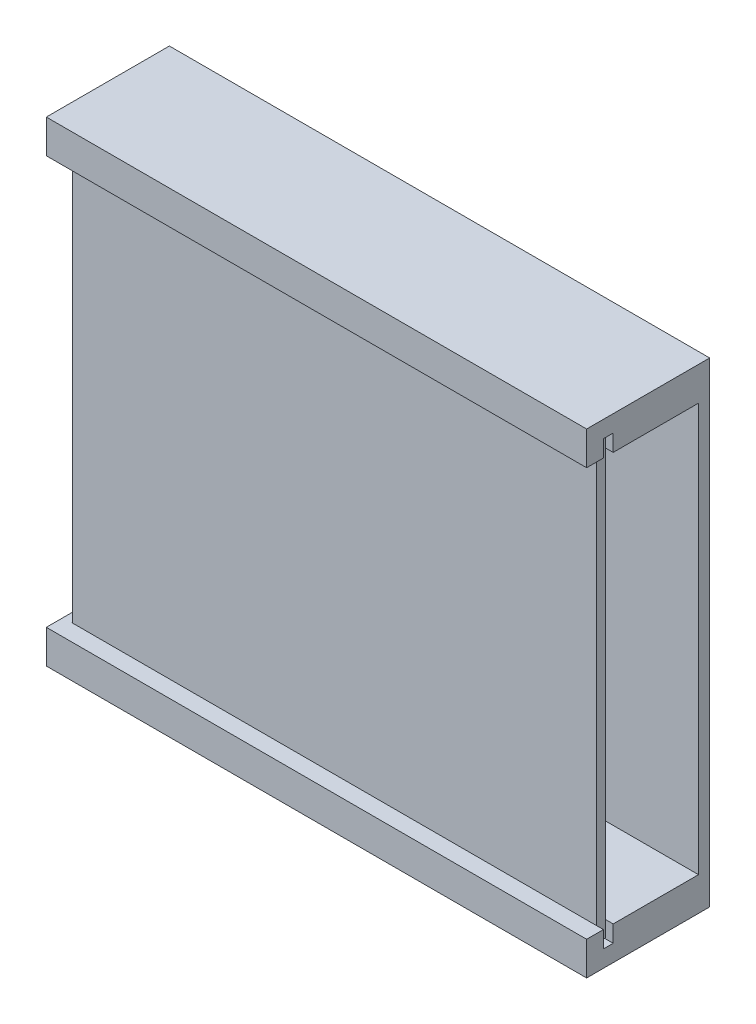
SolidWorks part; units mm, degrees
ref_plane "Front Plane" through (0, 0, 0) normal (0, 0, 1) x (1, 0, 0)
ref_plane "Top Plane" through (0, 0, 0) normal (0, 1, 0) x (1, 0, 0)
ref_plane "Right Plane" through (0, 0, 0) normal (1, 0, 0) x (0, 0, -1)
sketch "Sketch2" plane through (0, 0, 0) normal (0, 0, 1) x (1, 0, 0)
  line L0 (129.413, 116.586) -> (129.54, 116.459)
  line L1 (129.54, 116.459) -> (129.54, 38.1)
  line L2 (129.54, 38.1) -> (35.687, 38.1)
  line L3 (35.687, 38.1) -> (35.56, 38.227)
  line L4 (35.56, 38.227) -> (36.195, 116.586)
  line L5 (36.195, 116.586) -> (129.413, 116.586)
  line L6 (106.7691, 112.8424) -> (106.543, 112.903)
  line L7 (106.543, 112.903) -> (106.4895, 112.903)
  line L8 (106.4895, 112.903) -> (106.4895, 112.0775)
  line L9 (106.4895, 112.0775) -> (107.315, 112.0775)
  line L10 (107.315, 112.0775) -> (107.315, 112.131)
  line L11 (107.315, 112.131) -> (107.2544, 112.3571)
  line L12 (107.2544, 112.3571) -> (107.1374, 112.5599)
  line L13 (107.1374, 112.5599) -> (106.9719, 112.7254)
  line L14 (106.9719, 112.7254) -> (106.7691, 112.8424)
  line L15 (106.3625, 112.0775) -> (106.3625, 112.903)
  line L16 (106.3625, 112.903) -> (106.309, 112.903)
  line L17 (106.309, 112.903) -> (106.0829, 112.8424)
  line L18 (106.0829, 112.8424) -> (105.8801, 112.7254)
  line L19 (105.8801, 112.7254) -> (105.7146, 112.5599)
  line L20 (105.7146, 112.5599) -> (105.5976, 112.3571)
  line L21 (105.5976, 112.3571) -> (105.537, 112.131)
  line L22 (105.537, 112.131) -> (105.537, 112.0775)
  line L23 (105.537, 112.0775) -> (106.3625, 112.0775)
  line L24 (116.9291, 112.8424) -> (116.703, 112.903)
  line L25 (116.703, 112.903) -> (116.469, 112.903)
  line L26 (116.469, 112.903) -> (116.2429, 112.8424)
  line L27 (116.2429, 112.8424) -> (116.0401, 112.7254)
  line L28 (116.0401, 112.7254) -> (115.8746, 112.5599)
  line L29 (115.8746, 112.5599) -> (115.7576, 112.3571)
  line L30 (115.7576, 112.3571) -> (115.697, 112.131)
  line L31 (115.697, 112.131) -> (115.697, 111.897)
  line L32 (115.697, 111.897) -> (115.7576, 111.6709)
  line L33 (115.7576, 111.6709) -> (115.8746, 111.4681)
  line L34 (115.8746, 111.4681) -> (116.0401, 111.3026)
  line L35 (116.0401, 111.3026) -> (116.2429, 111.1856)
  line L36 (116.2429, 111.1856) -> (116.469, 111.125)
  line L37 (116.469, 111.125) -> (116.703, 111.125)
  line L38 (116.703, 111.125) -> (116.9291, 111.1856)
  line L39 (116.9291, 111.1856) -> (117.1319, 111.3026)
  line L40 (117.1319, 111.3026) -> (117.2974, 111.4681)
  line L41 (117.2974, 111.4681) -> (117.4144, 111.6709)
  line L42 (117.4144, 111.6709) -> (117.475, 111.897)
  line L43 (117.475, 111.897) -> (117.475, 112.131)
  line L44 (117.475, 112.131) -> (117.4144, 112.3571)
  line L45 (117.4144, 112.3571) -> (117.2974, 112.5599)
  line L46 (117.2974, 112.5599) -> (117.1319, 112.7254)
  line L47 (117.1319, 112.7254) -> (116.9291, 112.8424)
  line L48 (114.3891, 112.8424) -> (114.163, 112.903)
  line L49 (114.163, 112.903) -> (113.929, 112.903)
  line L50 (113.929, 112.903) -> (113.7029, 112.8424)
  line L51 (113.7029, 112.8424) -> (113.5001, 112.7254)
  line L52 (113.5001, 112.7254) -> (113.3346, 112.5599)
  line L53 (113.3346, 112.5599) -> (113.2176, 112.3571)
  line L54 (113.2176, 112.3571) -> (113.157, 112.131)
  line L55 (113.157, 112.131) -> (113.157, 111.897)
  line L56 (113.157, 111.897) -> (113.2176, 111.6709)
  line L57 (113.2176, 111.6709) -> (113.3346, 111.4681)
  line L58 (113.3346, 111.4681) -> (113.5001, 111.3026)
  line L59 (113.5001, 111.3026) -> (113.7029, 111.1856)
  line L60 (113.7029, 111.1856) -> (113.929, 111.125)
  line L61 (113.929, 111.125) -> (114.163, 111.125)
  line L62 (114.163, 111.125) -> (114.3891, 111.1856)
  line L63 (114.3891, 111.1856) -> (114.5919, 111.3026)
  line L64 (114.5919, 111.3026) -> (114.7574, 111.4681)
  line L65 (114.7574, 111.4681) -> (114.8744, 111.6709)
  line L66 (114.8744, 111.6709) -> (114.935, 111.897)
  line L67 (114.935, 111.897) -> (114.935, 112.131)
  line L68 (114.935, 112.131) -> (114.8744, 112.3571)
  line L69 (114.8744, 112.3571) -> (114.7574, 112.5599)
  line L70 (114.7574, 112.5599) -> (114.5919, 112.7254)
  line L71 (114.5919, 112.7254) -> (114.3891, 112.8424)
  line L72 (111.8491, 112.8424) -> (111.623, 112.903)
  line L73 (111.623, 112.903) -> (111.389, 112.903)
  line L74 (111.389, 112.903) -> (111.1629, 112.8424)
  line L75 (111.1629, 112.8424) -> (110.9601, 112.7254)
  line L76 (110.9601, 112.7254) -> (110.7946, 112.5599)
  line L77 (110.7946, 112.5599) -> (110.6776, 112.3571)
  line L78 (110.6776, 112.3571) -> (110.617, 112.131)
  line L79 (110.617, 112.131) -> (110.617, 111.897)
  line L80 (110.617, 111.897) -> (110.6776, 111.6709)
  line L81 (110.6776, 111.6709) -> (110.7946, 111.4681)
  line L82 (110.7946, 111.4681) -> (110.9601, 111.3026)
  line L83 (110.9601, 111.3026) -> (111.1629, 111.1856)
  line L84 (111.1629, 111.1856) -> (111.389, 111.125)
  line L85 (111.389, 111.125) -> (111.623, 111.125)
  line L86 (111.623, 111.125) -> (111.8491, 111.1856)
  line L87 (111.8491, 111.1856) -> (112.0519, 111.3026)
  line L88 (112.0519, 111.3026) -> (112.2174, 111.4681)
  line L89 (112.2174, 111.4681) -> (112.3344, 111.6709)
  line L90 (112.3344, 111.6709) -> (112.395, 111.897)
  line L91 (112.395, 111.897) -> (112.395, 112.131)
  line L92 (112.395, 112.131) -> (112.3344, 112.3571)
  line L93 (112.3344, 112.3571) -> (112.2174, 112.5599)
  line L94 (112.2174, 112.5599) -> (112.0519, 112.7254)
  line L95 (112.0519, 112.7254) -> (111.8491, 112.8424)
  line L96 (109.3091, 112.8424) -> (109.083, 112.903)
  line L97 (109.083, 112.903) -> (108.849, 112.903)
  line L98 (108.849, 112.903) -> (108.6229, 112.8424)
  line L99 (108.6229, 112.8424) -> (108.4201, 112.7254)
  line L100 (108.4201, 112.7254) -> (108.2546, 112.5599)
  line L101 (108.2546, 112.5599) -> (108.1376, 112.3571)
  line L102 (108.1376, 112.3571) -> (108.077, 112.131)
  line L103 (108.077, 112.131) -> (108.077, 111.897)
  line L104 (108.077, 111.897) -> (108.1376, 111.6709)
  line L105 (108.1376, 111.6709) -> (108.2546, 111.4681)
  line L106 (108.2546, 111.4681) -> (108.4201, 111.3026)
  line L107 (108.4201, 111.3026) -> (108.6229, 111.1856)
  line L108 (108.6229, 111.1856) -> (108.849, 111.125)
  line L109 (108.849, 111.125) -> (109.083, 111.125)
  line L110 (109.083, 111.125) -> (109.3091, 111.1856)
  line L111 (109.3091, 111.1856) -> (109.5119, 111.3026)
  line L112 (109.5119, 111.3026) -> (109.6774, 111.4681)
  line L113 (109.6774, 111.4681) -> (109.7944, 111.6709)
  line L114 (109.7944, 111.6709) -> (109.855, 111.897)
  line L115 (109.855, 111.897) -> (109.855, 112.131)
  line L116 (109.855, 112.131) -> (109.7944, 112.3571)
  line L117 (109.7944, 112.3571) -> (109.6774, 112.5599)
  line L118 (109.6774, 112.5599) -> (109.5119, 112.7254)
  line L119 (109.5119, 112.7254) -> (109.3091, 112.8424)
  line L120 (107.315, 111.897) -> (107.315, 111.9505)
  line L121 (107.315, 111.9505) -> (106.4895, 111.9505)
  line L122 (106.4895, 111.9505) -> (106.4895, 111.125)
  line L123 (106.4895, 111.125) -> (106.543, 111.125)
  line L124 (106.543, 111.125) -> (106.7691, 111.1856)
  line L125 (106.7691, 111.1856) -> (106.9719, 111.3026)
  line L126 (106.9719, 111.3026) -> (107.1374, 111.4681)
  line L127 (107.1374, 111.4681) -> (107.2544, 111.6709)
  line L128 (107.2544, 111.6709) -> (107.315, 111.897)
  line L129 (106.3625, 111.125) -> (106.3625, 111.9505)
  line L130 (106.3625, 111.9505) -> (105.537, 111.9505)
  line L131 (105.537, 111.9505) -> (105.537, 111.897)
  line L132 (105.537, 111.897) -> (105.5976, 111.6709)
  line L133 (105.5976, 111.6709) -> (105.7146, 111.4681)
  line L134 (105.7146, 111.4681) -> (105.8801, 111.3026)
  line L135 (105.8801, 111.3026) -> (106.0829, 111.1856)
  line L136 (106.0829, 111.1856) -> (106.309, 111.125)
  line L137 (106.309, 111.125) -> (106.3625, 111.125)
  line L138 (104.2291, 112.8424) -> (104.003, 112.903)
  line L139 (104.003, 112.903) -> (103.769, 112.903)
  line L140 (103.769, 112.903) -> (103.5429, 112.8424)
  line L141 (103.5429, 112.8424) -> (103.3401, 112.7254)
  line L142 (103.3401, 112.7254) -> (103.1746, 112.5599)
  line L143 (103.1746, 112.5599) -> (103.0576, 112.3571)
  line L144 (103.0576, 112.3571) -> (102.997, 112.131)
  line L145 (102.997, 112.131) -> (102.997, 111.897)
  line L146 (102.997, 111.897) -> (103.0576, 111.6709)
  line L147 (103.0576, 111.6709) -> (103.1746, 111.4681)
  line L148 (103.1746, 111.4681) -> (103.3401, 111.3026)
  line L149 (103.3401, 111.3026) -> (103.5429, 111.1856)
  line L150 (103.5429, 111.1856) -> (103.769, 111.125)
  line L151 (103.769, 111.125) -> (104.003, 111.125)
  line L152 (104.003, 111.125) -> (104.2291, 111.1856)
  line L153 (104.2291, 111.1856) -> (104.4319, 111.3026)
  line L154 (104.4319, 111.3026) -> (104.5974, 111.4681)
  line L155 (104.5974, 111.4681) -> (104.7144, 111.6709)
  line L156 (104.7144, 111.6709) -> (104.775, 111.897)
  line L157 (104.775, 111.897) -> (104.775, 112.131)
  line L158 (104.775, 112.131) -> (104.7144, 112.3571)
  line L159 (104.7144, 112.3571) -> (104.5974, 112.5599)
  line L160 (104.5974, 112.5599) -> (104.4319, 112.7254)
  line L161 (104.4319, 112.7254) -> (104.2291, 112.8424)
  line L162 (42.3801, 112.3344) -> (42.154, 112.395)
  line L163 (42.154, 112.395) -> (41.92, 112.395)
  line L164 (41.92, 112.395) -> (41.6939, 112.3344)
  line L165 (41.6939, 112.3344) -> (41.4911, 112.2174)
  line L166 (41.4911, 112.2174) -> (41.3256, 112.0519)
  line L167 (41.3256, 112.0519) -> (41.2086, 111.8491)
  line L168 (41.2086, 111.8491) -> (41.148, 111.623)
  line L169 (41.148, 111.623) -> (41.148, 111.389)
  line L170 (41.148, 111.389) -> (41.2086, 111.1629)
  line L171 (41.2086, 111.1629) -> (41.3256, 110.9601)
  line L172 (41.3256, 110.9601) -> (41.4911, 110.7946)
  line L173 (41.4911, 110.7946) -> (41.6939, 110.6776)
  line L174 (41.6939, 110.6776) -> (41.92, 110.617)
  line L175 (41.92, 110.617) -> (42.154, 110.617)
  line L176 (42.154, 110.617) -> (42.3801, 110.6776)
  line L177 (42.3801, 110.6776) -> (42.5829, 110.7946)
  line L178 (42.5829, 110.7946) -> (42.7484, 110.9601)
  line L179 (42.7484, 110.9601) -> (42.8654, 111.1629)
  line L180 (42.8654, 111.1629) -> (42.926, 111.389)
  line L181 (42.926, 111.389) -> (42.926, 111.623)
  line L182 (42.926, 111.623) -> (42.8654, 111.8491)
  line L183 (42.8654, 111.8491) -> (42.7484, 112.0519)
  line L184 (42.7484, 112.0519) -> (42.5829, 112.2174)
  line L185 (42.5829, 112.2174) -> (42.3801, 112.3344)
  line L186 (42.3801, 109.7944) -> (42.154, 109.855)
  line L187 (42.154, 109.855) -> (41.92, 109.855)
  line L188 (41.92, 109.855) -> (41.6939, 109.7944)
  line L189 (41.6939, 109.7944) -> (41.4911, 109.6774)
  line L190 (41.4911, 109.6774) -> (41.3256, 109.5119)
  line L191 (41.3256, 109.5119) -> (41.2086, 109.3091)
  line L192 (41.2086, 109.3091) -> (41.148, 109.083)
  line L193 (41.148, 109.083) -> (41.148, 108.849)
  line L194 (41.148, 108.849) -> (41.2086, 108.6229)
  line L195 (41.2086, 108.6229) -> (41.3256, 108.4201)
  line L196 (41.3256, 108.4201) -> (41.4911, 108.2546)
  line L197 (41.4911, 108.2546) -> (41.6939, 108.1376)
  line L198 (41.6939, 108.1376) -> (41.92, 108.077)
  line L199 (41.92, 108.077) -> (42.154, 108.077)
  line L200 (42.154, 108.077) -> (42.3801, 108.1376)
  line L201 (42.3801, 108.1376) -> (42.5829, 108.2546)
  line L202 (42.5829, 108.2546) -> (42.7484, 108.4201)
  line L203 (42.7484, 108.4201) -> (42.8654, 108.6229)
  line L204 (42.8654, 108.6229) -> (42.926, 108.849)
  line L205 (42.926, 108.849) -> (42.926, 109.083)
  line L206 (42.926, 109.083) -> (42.8654, 109.3091)
  line L207 (42.8654, 109.3091) -> (42.7484, 109.5119)
  line L208 (42.7484, 109.5119) -> (42.5829, 109.6774)
  line L209 (42.5829, 109.6774) -> (42.3801, 109.7944)
  line L210 (42.3801, 107.2544) -> (42.154, 107.315)
  line L211 (42.154, 107.315) -> (41.92, 107.315)
  line L212 (41.92, 107.315) -> (41.6939, 107.2544)
  line L213 (41.6939, 107.2544) -> (41.4911, 107.1374)
  line L214 (41.4911, 107.1374) -> (41.3256, 106.9719)
  line L215 (41.3256, 106.9719) -> (41.2086, 106.7691)
  line L216 (41.2086, 106.7691) -> (41.148, 106.543)
  line L217 (41.148, 106.543) -> (41.148, 106.309)
  line L218 (41.148, 106.309) -> (41.2086, 106.0829)
  line L219 (41.2086, 106.0829) -> (41.3256, 105.8801)
  line L220 (41.3256, 105.8801) -> (41.4911, 105.7146)
  line L221 (41.4911, 105.7146) -> (41.6939, 105.5976)
  line L222 (41.6939, 105.5976) -> (41.92, 105.537)
  line L223 (41.92, 105.537) -> (42.154, 105.537)
  line L224 (42.154, 105.537) -> (42.3801, 105.5976)
  line L225 (42.3801, 105.5976) -> (42.5829, 105.7146)
  line L226 (42.5829, 105.7146) -> (42.7484, 105.8801)
  line L227 (42.7484, 105.8801) -> (42.8654, 106.0829)
  line L228 (42.8654, 106.0829) -> (42.926, 106.309)
  line L229 (42.926, 106.309) -> (42.926, 106.543)
  line L230 (42.926, 106.543) -> (42.8654, 106.7691)
  line L231 (42.8654, 106.7691) -> (42.7484, 106.9719)
  line L232 (42.7484, 106.9719) -> (42.5829, 107.1374)
  line L233 (42.5829, 107.1374) -> (42.3801, 107.2544)
  line L234 (125.0571, 106.2384) -> (124.831, 106.299)
  line L235 (124.831, 106.299) -> (124.7775, 106.299)
  line L236 (124.7775, 106.299) -> (124.7775, 105.4735)
  line L237 (124.7775, 105.4735) -> (125.603, 105.4735)
  line L238 (125.603, 105.4735) -> (125.603, 105.527)
  line L239 (125.603, 105.527) -> (125.5424, 105.7531)
  line L240 (125.5424, 105.7531) -> (125.4254, 105.9559)
  line L241 (125.4254, 105.9559) -> (125.2599, 106.1214)
  line L242 (125.2599, 106.1214) -> (125.0571, 106.2384)
  line L243 (124.6505, 105.4735) -> (124.6505, 106.299)
  line L244 (124.6505, 106.299) -> (124.597, 106.299)
  line L245 (124.597, 106.299) -> (124.3709, 106.2384)
  line L246 (124.3709, 106.2384) -> (124.1681, 106.1214)
  line L247 (124.1681, 106.1214) -> (124.0026, 105.9559)
  line L248 (124.0026, 105.9559) -> (123.8856, 105.7531)
  line L249 (123.8856, 105.7531) -> (123.825, 105.527)
  line L250 (123.825, 105.527) -> (123.825, 105.4735)
  line L251 (123.825, 105.4735) -> (124.6505, 105.4735)
  line L252 (125.603, 105.293) -> (125.603, 105.3465)
  line L253 (125.603, 105.3465) -> (124.7775, 105.3465)
  line L254 (124.7775, 105.3465) -> (124.7775, 104.521)
  line L255 (124.7775, 104.521) -> (124.831, 104.521)
  line L256 (124.831, 104.521) -> (125.0571, 104.5816)
  line L257 (125.0571, 104.5816) -> (125.2599, 104.6986)
  line L258 (125.2599, 104.6986) -> (125.4254, 104.8641)
  line L259 (125.4254, 104.8641) -> (125.5424, 105.0669)
  line L260 (125.5424, 105.0669) -> (125.603, 105.293)
  line L261 (124.6505, 104.521) -> (124.6505, 105.3465)
  line L262 (124.6505, 105.3465) -> (123.825, 105.3465)
  line L263 (123.825, 105.3465) -> (123.825, 105.293)
  line L264 (123.825, 105.293) -> (123.8856, 105.0669)
  line L265 (123.8856, 105.0669) -> (124.0026, 104.8641)
  line L266 (124.0026, 104.8641) -> (124.1681, 104.6986)
  line L267 (124.1681, 104.6986) -> (124.3709, 104.5816)
  line L268 (124.3709, 104.5816) -> (124.597, 104.521)
  line L269 (124.597, 104.521) -> (124.6505, 104.521)
  line L270 (42.3801, 104.7144) -> (42.154, 104.775)
  line L271 (42.154, 104.775) -> (41.92, 104.775)
  line L272 (41.92, 104.775) -> (41.6939, 104.7144)
  line L273 (41.6939, 104.7144) -> (41.4911, 104.5974)
  line L274 (41.4911, 104.5974) -> (41.3256, 104.4319)
  line L275 (41.3256, 104.4319) -> (41.2086, 104.2291)
  line L276 (41.2086, 104.2291) -> (41.148, 104.003)
  line L277 (41.148, 104.003) -> (41.148, 103.769)
  line L278 (41.148, 103.769) -> (41.2086, 103.5429)
  line L279 (41.2086, 103.5429) -> (41.3256, 103.3401)
  line L280 (41.3256, 103.3401) -> (41.4911, 103.1746)
  line L281 (41.4911, 103.1746) -> (41.6939, 103.0576)
  line L282 (41.6939, 103.0576) -> (41.92, 102.997)
  line L283 (41.92, 102.997) -> (42.154, 102.997)
  line L284 (42.154, 102.997) -> (42.3801, 103.0576)
  line L285 (42.3801, 103.0576) -> (42.5829, 103.1746)
  line L286 (42.5829, 103.1746) -> (42.7484, 103.3401)
  line L287 (42.7484, 103.3401) -> (42.8654, 103.5429)
  line L288 (42.8654, 103.5429) -> (42.926, 103.769)
  line L289 (42.926, 103.769) -> (42.926, 104.003)
  line L290 (42.926, 104.003) -> (42.8654, 104.2291)
  line L291 (42.8654, 104.2291) -> (42.7484, 104.4319)
  line L292 (42.7484, 104.4319) -> (42.5829, 104.5974)
  line L293 (42.5829, 104.5974) -> (42.3801, 104.7144)
  line L294 (100.0381, 104.3334) -> (99.812, 104.394)
  line L295 (99.812, 104.394) -> (99.578, 104.394)
  line L296 (99.578, 104.394) -> (99.3519, 104.3334)
  line L297 (99.3519, 104.3334) -> (99.1491, 104.2164)
  line L298 (99.1491, 104.2164) -> (98.9836, 104.0509)
  line L299 (98.9836, 104.0509) -> (98.8666, 103.8481)
  line L300 (98.8666, 103.8481) -> (98.806, 103.622)
  line L301 (98.806, 103.622) -> (98.806, 103.388)
  line L302 (98.806, 103.388) -> (98.8666, 103.1619)
  line L303 (98.8666, 103.1619) -> (98.9836, 102.9591)
  line L304 (98.9836, 102.9591) -> (99.1491, 102.7936)
  line L305 (99.1491, 102.7936) -> (99.3519, 102.6766)
  line L306 (99.3519, 102.6766) -> (99.578, 102.616)
  line L307 (99.578, 102.616) -> (99.812, 102.616)
  line L308 (99.812, 102.616) -> (100.0381, 102.6766)
  line L309 (100.0381, 102.6766) -> (100.2409, 102.7936)
  line L310 (100.2409, 102.7936) -> (100.4064, 102.9591)
  line L311 (100.4064, 102.9591) -> (100.5234, 103.1619)
  line L312 (100.5234, 103.1619) -> (100.584, 103.388)
  line L313 (100.584, 103.388) -> (100.584, 103.622)
  line L314 (100.584, 103.622) -> (100.5234, 103.8481)
  line L315 (100.5234, 103.8481) -> (100.4064, 104.0509)
  line L316 (100.4064, 104.0509) -> (100.2409, 104.2164)
  line L317 (100.2409, 104.2164) -> (100.0381, 104.3334)
  line L318 (77.1781, 104.3334) -> (76.952, 104.394)
  line L319 (76.952, 104.394) -> (76.718, 104.394)
  line L320 (76.718, 104.394) -> (76.4919, 104.3334)
  line L321 (76.4919, 104.3334) -> (76.2891, 104.2164)
  line L322 (76.2891, 104.2164) -> (76.1236, 104.0509)
  line L323 (76.1236, 104.0509) -> (76.0066, 103.8481)
  line L324 (76.0066, 103.8481) -> (75.946, 103.622)
  line L325 (75.946, 103.622) -> (75.946, 103.388)
  line L326 (75.946, 103.388) -> (76.0066, 103.1619)
  line L327 (76.0066, 103.1619) -> (76.1236, 102.9591)
  line L328 (76.1236, 102.9591) -> (76.2891, 102.7936)
  line L329 (76.2891, 102.7936) -> (76.4919, 102.6766)
  line L330 (76.4919, 102.6766) -> (76.718, 102.616)
  line L331 (76.718, 102.616) -> (76.952, 102.616)
  line L332 (76.952, 102.616) -> (77.1781, 102.6766)
  line L333 (77.1781, 102.6766) -> (77.3809, 102.7936)
  line L334 (77.3809, 102.7936) -> (77.5464, 102.9591)
  line L335 (77.5464, 102.9591) -> (77.6634, 103.1619)
  line L336 (77.6634, 103.1619) -> (77.724, 103.388)
  line L337 (77.724, 103.388) -> (77.724, 103.622)
  line L338 (77.724, 103.622) -> (77.6634, 103.8481)
  line L339 (77.6634, 103.8481) -> (77.5464, 104.0509)
  line L340 (77.5464, 104.0509) -> (77.3809, 104.2164)
  line L341 (77.3809, 104.2164) -> (77.1781, 104.3334)
  line L342 (102.7132, 110.5872) -> (102.616, 110.6275)
  line L343 (102.616, 110.6275) -> (68.961, 110.6275)
  line L344 (68.961, 110.6275) -> (68.8638, 110.5872)
  line L345 (68.8638, 110.5872) -> (66.5778, 108.3012)
  line L346 (66.5778, 108.3012) -> (66.5375, 108.204)
  line L347 (66.5375, 108.204) -> (66.5375, 100.33)
  line L348 (66.5375, 100.33) -> (66.5778, 100.2328)
  line L349 (66.5778, 100.2328) -> (66.675, 100.1925)
  line L350 (66.675, 100.1925) -> (73.914, 100.1925)
  line L351 (73.914, 100.1925) -> (74.0112, 100.2328)
  line L352 (74.0112, 100.2328) -> (74.1382, 100.3598)
  line L353 (74.1382, 100.3598) -> (74.1785, 100.457)
  line L354 (74.1785, 100.457) -> (74.1785, 104.8451)
  line L355 (74.1785, 104.8451) -> (74.8599, 105.5265)
  line L356 (74.8599, 105.5265) -> (77.7941, 105.5265)
  line L357 (77.7941, 105.5265) -> (78.7295, 104.5911)
  line L358 (78.7295, 104.5911) -> (78.7295, 98.552)
  line L359 (78.7295, 98.552) -> (78.7295, 98.425)
  line L360 (78.7295, 98.425) -> (78.7698, 98.3278)
  line L361 (78.7698, 98.3278) -> (78.867, 98.2875)
  line L362 (78.867, 98.2875) -> (97.663, 98.2875)
  line L363 (97.663, 98.2875) -> (97.7602, 98.3278)
  line L364 (97.7602, 98.3278) -> (97.8005, 98.425)
  line L365 (97.8005, 98.425) -> (97.8005, 105.41)
  line L366 (97.8005, 105.41) -> (97.8897, 105.5265)
  line L367 (97.8897, 105.5265) -> (101.7165, 105.5265)
  line L368 (101.7165, 105.5265) -> (101.7165, 102.87)
  line L369 (101.7165, 102.87) -> (101.7568, 102.7728)
  line L370 (101.7568, 102.7728) -> (101.8838, 102.6458)
  line L371 (101.8838, 102.6458) -> (101.9609, 102.6139)
  line L372 (101.9609, 102.6139) -> (101.981, 102.6055)
  line L373 (101.981, 102.6055) -> (102.0782, 102.6458)
  line L374 (102.0782, 102.6458) -> (103.7292, 104.2968)
  line L375 (103.7292, 104.2968) -> (103.7695, 104.394)
  line L376 (103.7695, 104.394) -> (103.7695, 109.474)
  line L377 (103.7695, 109.474) -> (103.7292, 109.5712)
  line L378 (103.7292, 109.5712) -> (102.7132, 110.5872)
  line L379 (125.0571, 103.6984) -> (124.831, 103.759)
  line L380 (124.831, 103.759) -> (124.597, 103.759)
  line L381 (124.597, 103.759) -> (124.3709, 103.6984)
  line L382 (124.3709, 103.6984) -> (124.1681, 103.5814)
  line L383 (124.1681, 103.5814) -> (124.0026, 103.4159)
  line L384 (124.0026, 103.4159) -> (123.8856, 103.2131)
  line L385 (123.8856, 103.2131) -> (123.825, 102.987)
  line L386 (123.825, 102.987) -> (123.825, 102.753)
  line L387 (123.825, 102.753) -> (123.8856, 102.5269)
  line L388 (123.8856, 102.5269) -> (124.0026, 102.3241)
  line L389 (124.0026, 102.3241) -> (124.1681, 102.1586)
  line L390 (124.1681, 102.1586) -> (124.3709, 102.0416)
  line L391 (124.3709, 102.0416) -> (124.597, 101.981)
  line L392 (124.597, 101.981) -> (124.831, 101.981)
  line L393 (124.831, 101.981) -> (125.0571, 102.0416)
  line L394 (125.0571, 102.0416) -> (125.2599, 102.1586)
  line L395 (125.2599, 102.1586) -> (125.4254, 102.3241)
  line L396 (125.4254, 102.3241) -> (125.5424, 102.5269)
  line L397 (125.5424, 102.5269) -> (125.603, 102.753)
  line L398 (125.603, 102.753) -> (125.603, 102.987)
  line L399 (125.603, 102.987) -> (125.5424, 103.2131)
  line L400 (125.5424, 103.2131) -> (125.4254, 103.4159)
  line L401 (125.4254, 103.4159) -> (125.2599, 103.5814)
  line L402 (125.2599, 103.5814) -> (125.0571, 103.6984)
  line L403 (42.3801, 102.1744) -> (42.154, 102.235)
  line L404 (42.154, 102.235) -> (41.92, 102.235)
  line L405 (41.92, 102.235) -> (41.6939, 102.1744)
  line L406 (41.6939, 102.1744) -> (41.4911, 102.0574)
  line L407 (41.4911, 102.0574) -> (41.3256, 101.8919)
  line L408 (41.3256, 101.8919) -> (41.2086, 101.6891)
  line L409 (41.2086, 101.6891) -> (41.148, 101.463)
  line L410 (41.148, 101.463) -> (41.148, 101.229)
  line L411 (41.148, 101.229) -> (41.2086, 101.0029)
  line L412 (41.2086, 101.0029) -> (41.3256, 100.8001)
  line L413 (41.3256, 100.8001) -> (41.4911, 100.6346)
  line L414 (41.4911, 100.6346) -> (41.6939, 100.5176)
  line L415 (41.6939, 100.5176) -> (41.92, 100.457)
  line L416 (41.92, 100.457) -> (42.154, 100.457)
  line L417 (42.154, 100.457) -> (42.3801, 100.5176)
  line L418 (42.3801, 100.5176) -> (42.5829, 100.6346)
  line L419 (42.5829, 100.6346) -> (42.7484, 100.8001)
  line L420 (42.7484, 100.8001) -> (42.8654, 101.0029)
  line L421 (42.8654, 101.0029) -> (42.926, 101.229)
  line L422 (42.926, 101.229) -> (42.926, 101.463)
  line L423 (42.926, 101.463) -> (42.8654, 101.6891)
  line L424 (42.8654, 101.6891) -> (42.7484, 101.8919)
  line L425 (42.7484, 101.8919) -> (42.5829, 102.0574)
  line L426 (42.5829, 102.0574) -> (42.3801, 102.1744)
  line L427 (100.0381, 101.7934) -> (99.812, 101.854)
  line L428 (99.812, 101.854) -> (99.578, 101.854)
  line L429 (99.578, 101.854) -> (99.3519, 101.7934)
  line L430 (99.3519, 101.7934) -> (99.1491, 101.6764)
  line L431 (99.1491, 101.6764) -> (98.9836, 101.5109)
  line L432 (98.9836, 101.5109) -> (98.8666, 101.3081)
  line L433 (98.8666, 101.3081) -> (98.806, 101.082)
  line L434 (98.806, 101.082) -> (98.806, 100.848)
  line L435 (98.806, 100.848) -> (98.8666, 100.6219)
  line L436 (98.8666, 100.6219) -> (98.9836, 100.4191)
  line L437 (98.9836, 100.4191) -> (99.1491, 100.2536)
  line L438 (99.1491, 100.2536) -> (99.3519, 100.1366)
  line L439 (99.3519, 100.1366) -> (99.578, 100.076)
  line L440 (99.578, 100.076) -> (99.812, 100.076)
  line L441 (99.812, 100.076) -> (100.0381, 100.1366)
  line L442 (100.0381, 100.1366) -> (100.2409, 100.2536)
  line L443 (100.2409, 100.2536) -> (100.4064, 100.4191)
  line L444 (100.4064, 100.4191) -> (100.5234, 100.6219)
  line L445 (100.5234, 100.6219) -> (100.584, 100.848)
  line L446 (100.584, 100.848) -> (100.584, 101.082)
  line L447 (100.584, 101.082) -> (100.5234, 101.3081)
  line L448 (100.5234, 101.3081) -> (100.4064, 101.5109)
  line L449 (100.4064, 101.5109) -> (100.2409, 101.6764)
  line L450 (100.2409, 101.6764) -> (100.0381, 101.7934)
  line L451 (77.1781, 101.7934) -> (76.952, 101.854)
  line L452 (76.952, 101.854) -> (76.718, 101.854)
  line L453 (76.718, 101.854) -> (76.4919, 101.7934)
  line L454 (76.4919, 101.7934) -> (76.2891, 101.6764)
  line L455 (76.2891, 101.6764) -> (76.1236, 101.5109)
  line L456 (76.1236, 101.5109) -> (76.0066, 101.3081)
  line L457 (76.0066, 101.3081) -> (75.946, 101.082)
  line L458 (75.946, 101.082) -> (75.946, 100.848)
  line L459 (75.946, 100.848) -> (76.0066, 100.6219)
  line L460 (76.0066, 100.6219) -> (76.1236, 100.4191)
  line L461 (76.1236, 100.4191) -> (76.2891, 100.2536)
  line L462 (76.2891, 100.2536) -> (76.4919, 100.1366)
  line L463 (76.4919, 100.1366) -> (76.718, 100.076)
  line L464 (76.718, 100.076) -> (76.952, 100.076)
  line L465 (76.952, 100.076) -> (77.1781, 100.1366)
  line L466 (77.1781, 100.1366) -> (77.3809, 100.2536)
  line L467 (77.3809, 100.2536) -> (77.5464, 100.4191)
  line L468 (77.5464, 100.4191) -> (77.6634, 100.6219)
  line L469 (77.6634, 100.6219) -> (77.724, 100.848)
  line L470 (77.724, 100.848) -> (77.724, 101.082)
  line L471 (77.724, 101.082) -> (77.6634, 101.3081)
  line L472 (77.6634, 101.3081) -> (77.5464, 101.5109)
  line L473 (77.5464, 101.5109) -> (77.3809, 101.6764)
  line L474 (77.3809, 101.6764) -> (77.1781, 101.7934)
  line L475 (125.0571, 101.1584) -> (124.831, 101.219)
  line L476 (124.831, 101.219) -> (124.597, 101.219)
  line L477 (124.597, 101.219) -> (124.3709, 101.1584)
  line L478 (124.3709, 101.1584) -> (124.1681, 101.0414)
  line L479 (124.1681, 101.0414) -> (124.0026, 100.8759)
  line L480 (124.0026, 100.8759) -> (123.8856, 100.6731)
  line L481 (123.8856, 100.6731) -> (123.825, 100.447)
  line L482 (123.825, 100.447) -> (123.825, 100.213)
  line L483 (123.825, 100.213) -> (123.8856, 99.9869)
  line L484 (123.8856, 99.9869) -> (124.0026, 99.7841)
  line L485 (124.0026, 99.7841) -> (124.1681, 99.6186)
  line L486 (124.1681, 99.6186) -> (124.3709, 99.5016)
  line L487 (124.3709, 99.5016) -> (124.597, 99.441)
  line L488 (124.597, 99.441) -> (124.831, 99.441)
  line L489 (124.831, 99.441) -> (125.0571, 99.5016)
  line L490 (125.0571, 99.5016) -> (125.2599, 99.6186)
  line L491 (125.2599, 99.6186) -> (125.4254, 99.7841)
  line L492 (125.4254, 99.7841) -> (125.5424, 99.9869)
  line L493 (125.5424, 99.9869) -> (125.603, 100.213)
  line L494 (125.603, 100.213) -> (125.603, 100.447)
  line L495 (125.603, 100.447) -> (125.5424, 100.6731)
  line L496 (125.5424, 100.6731) -> (125.4254, 100.8759)
  line L497 (125.4254, 100.8759) -> (125.2599, 101.0414)
  line L498 (125.2599, 101.0414) -> (125.0571, 101.1584)
  line L499 (42.3801, 99.6344) -> (42.154, 99.695)
  line L500 (42.154, 99.695) -> (41.92, 99.695)
  line L501 (41.92, 99.695) -> (41.6939, 99.6344)
  line L502 (41.6939, 99.6344) -> (41.4911, 99.5174)
  line L503 (41.4911, 99.5174) -> (41.3256, 99.3519)
  line L504 (41.3256, 99.3519) -> (41.2086, 99.1491)
  line L505 (41.2086, 99.1491) -> (41.148, 98.923)
  line L506 (41.148, 98.923) -> (41.148, 98.689)
  line L507 (41.148, 98.689) -> (41.2086, 98.4629)
  line L508 (41.2086, 98.4629) -> (41.3256, 98.2601)
  line L509 (41.3256, 98.2601) -> (41.4911, 98.0946)
  line L510 (41.4911, 98.0946) -> (41.6939, 97.9776)
  line L511 (41.6939, 97.9776) -> (41.92, 97.917)
  line L512 (41.92, 97.917) -> (42.154, 97.917)
  line L513 (42.154, 97.917) -> (42.3801, 97.9776)
  line L514 (42.3801, 97.9776) -> (42.5829, 98.0946)
  line L515 (42.5829, 98.0946) -> (42.7484, 98.2601)
  line L516 (42.7484, 98.2601) -> (42.8654, 98.4629)
  line L517 (42.8654, 98.4629) -> (42.926, 98.689)
  line L518 (42.926, 98.689) -> (42.926, 98.923)
  line L519 (42.926, 98.923) -> (42.8654, 99.1491)
  line L520 (42.8654, 99.1491) -> (42.7484, 99.3519)
  line L521 (42.7484, 99.3519) -> (42.5829, 99.5174)
  line L522 (42.5829, 99.5174) -> (42.3801, 99.6344)
  line L523 (100.0381, 99.2534) -> (99.812, 99.314)
  line L524 (99.812, 99.314) -> (99.578, 99.314)
  line L525 (99.578, 99.314) -> (99.3519, 99.2534)
  line L526 (99.3519, 99.2534) -> (99.1491, 99.1364)
  line L527 (99.1491, 99.1364) -> (98.9836, 98.9709)
  line L528 (98.9836, 98.9709) -> (98.8666, 98.7681)
  line L529 (98.8666, 98.7681) -> (98.806, 98.542)
  line L530 (98.806, 98.542) -> (98.806, 98.308)
  line L531 (98.806, 98.308) -> (98.8666, 98.0819)
  line L532 (98.8666, 98.0819) -> (98.9836, 97.8791)
  line L533 (98.9836, 97.8791) -> (99.1491, 97.7136)
  line L534 (99.1491, 97.7136) -> (99.3519, 97.5966)
  line L535 (99.3519, 97.5966) -> (99.578, 97.536)
  line L536 (99.578, 97.536) -> (99.812, 97.536)
  line L537 (99.812, 97.536) -> (100.0381, 97.5966)
  line L538 (100.0381, 97.5966) -> (100.2409, 97.7136)
  line L539 (100.2409, 97.7136) -> (100.4064, 97.8791)
  line L540 (100.4064, 97.8791) -> (100.5234, 98.0819)
  line L541 (100.5234, 98.0819) -> (100.584, 98.308)
  line L542 (100.584, 98.308) -> (100.584, 98.542)
  line L543 (100.584, 98.542) -> (100.5234, 98.7681)
  line L544 (100.5234, 98.7681) -> (100.4064, 98.9709)
  line L545 (100.4064, 98.9709) -> (100.2409, 99.1364)
  line L546 (100.2409, 99.1364) -> (100.0381, 99.2534)
  line L547 (77.1781, 99.2534) -> (76.952, 99.314)
  line L548 (76.952, 99.314) -> (76.718, 99.314)
  line L549 (76.718, 99.314) -> (76.4919, 99.2534)
  line L550 (76.4919, 99.2534) -> (76.2891, 99.1364)
  line L551 (76.2891, 99.1364) -> (76.1236, 98.9709)
  line L552 (76.1236, 98.9709) -> (76.0066, 98.7681)
  line L553 (76.0066, 98.7681) -> (75.946, 98.542)
  line L554 (75.946, 98.542) -> (75.946, 98.308)
  line L555 (75.946, 98.308) -> (76.0066, 98.0819)
  line L556 (76.0066, 98.0819) -> (76.1236, 97.8791)
  line L557 (76.1236, 97.8791) -> (76.2891, 97.7136)
  line L558 (76.2891, 97.7136) -> (76.4919, 97.5966)
  line L559 (76.4919, 97.5966) -> (76.718, 97.536)
  line L560 (76.718, 97.536) -> (76.952, 97.536)
  line L561 (76.952, 97.536) -> (77.1781, 97.5966)
  line L562 (77.1781, 97.5966) -> (77.3809, 97.7136)
  line L563 (77.3809, 97.7136) -> (77.5464, 97.8791)
  line L564 (77.5464, 97.8791) -> (77.6634, 98.0819)
  line L565 (77.6634, 98.0819) -> (77.724, 98.308)
  line L566 (77.724, 98.308) -> (77.724, 98.542)
  line L567 (77.724, 98.542) -> (77.6634, 98.7681)
  line L568 (77.6634, 98.7681) -> (77.5464, 98.9709)
  line L569 (77.5464, 98.9709) -> (77.3809, 99.1364)
  line L570 (77.3809, 99.1364) -> (77.1781, 99.2534)
  line L571 (125.0571, 98.6184) -> (124.831, 98.679)
  line L572 (124.831, 98.679) -> (124.597, 98.679)
  line L573 (124.597, 98.679) -> (124.3709, 98.6184)
  line L574 (124.3709, 98.6184) -> (124.1681, 98.5014)
  line L575 (124.1681, 98.5014) -> (124.0026, 98.3359)
  line L576 (124.0026, 98.3359) -> (123.8856, 98.1331)
  line L577 (123.8856, 98.1331) -> (123.825, 97.907)
  line L578 (123.825, 97.907) -> (123.825, 97.673)
  line L579 (123.825, 97.673) -> (123.8856, 97.4469)
  line L580 (123.8856, 97.4469) -> (124.0026, 97.2441)
  line L581 (124.0026, 97.2441) -> (124.1681, 97.0786)
  line L582 (124.1681, 97.0786) -> (124.3709, 96.9616)
  line L583 (124.3709, 96.9616) -> (124.597, 96.901)
  line L584 (124.597, 96.901) -> (124.831, 96.901)
  line L585 (124.831, 96.901) -> (125.0571, 96.9616)
  line L586 (125.0571, 96.9616) -> (125.2599, 97.0786)
  line L587 (125.2599, 97.0786) -> (125.4254, 97.2441)
  line L588 (125.4254, 97.2441) -> (125.5424, 97.4469)
  line L589 (125.5424, 97.4469) -> (125.603, 97.673)
  line L590 (125.603, 97.673) -> (125.603, 97.907)
  line L591 (125.603, 97.907) -> (125.5424, 98.1331)
  line L592 (125.5424, 98.1331) -> (125.4254, 98.3359)
  line L593 (125.4254, 98.3359) -> (125.2599, 98.5014)
  line L594 (125.2599, 98.5014) -> (125.0571, 98.6184)
  line L595 (42.3801, 97.0944) -> (42.154, 97.155)
  line L596 (42.154, 97.155) -> (41.92, 97.155)
  line L597 (41.92, 97.155) -> (41.6939, 97.0944)
  line L598 (41.6939, 97.0944) -> (41.4911, 96.9774)
  line L599 (41.4911, 96.9774) -> (41.3256, 96.8119)
  line L600 (41.3256, 96.8119) -> (41.2086, 96.6091)
  line L601 (41.2086, 96.6091) -> (41.148, 96.383)
  line L602 (41.148, 96.383) -> (41.148, 96.149)
  line L603 (41.148, 96.149) -> (41.2086, 95.9229)
  line L604 (41.2086, 95.9229) -> (41.3256, 95.7201)
  line L605 (41.3256, 95.7201) -> (41.4911, 95.5546)
  line L606 (41.4911, 95.5546) -> (41.6939, 95.4376)
  line L607 (41.6939, 95.4376) -> (41.92, 95.377)
  line L608 (41.92, 95.377) -> (42.154, 95.377)
  line L609 (42.154, 95.377) -> (42.3801, 95.4376)
  line L610 (42.3801, 95.4376) -> (42.5829, 95.5546)
  line L611 (42.5829, 95.5546) -> (42.7484, 95.7201)
  line L612 (42.7484, 95.7201) -> (42.8654, 95.9229)
  line L613 (42.8654, 95.9229) -> (42.926, 96.149)
  line L614 (42.926, 96.149) -> (42.926, 96.383)
  line L615 (42.926, 96.383) -> (42.8654, 96.6091)
  line L616 (42.8654, 96.6091) -> (42.7484, 96.8119)
  line L617 (42.7484, 96.8119) -> (42.5829, 96.9774)
  line L618 (42.5829, 96.9774) -> (42.3801, 97.0944)
  line L619 (100.0381, 96.7134) -> (99.812, 96.774)
  line L620 (99.812, 96.774) -> (99.578, 96.774)
  line L621 (99.578, 96.774) -> (99.3519, 96.7134)
  line L622 (99.3519, 96.7134) -> (99.1491, 96.5964)
  line L623 (99.1491, 96.5964) -> (98.9836, 96.4309)
  line L624 (98.9836, 96.4309) -> (98.8666, 96.2281)
  line L625 (98.8666, 96.2281) -> (98.806, 96.002)
  line L626 (98.806, 96.002) -> (98.806, 95.768)
  line L627 (98.806, 95.768) -> (98.8666, 95.5419)
  line L628 (98.8666, 95.5419) -> (98.9836, 95.3391)
  line L629 (98.9836, 95.3391) -> (99.1491, 95.1736)
  line L630 (99.1491, 95.1736) -> (99.3519, 95.0566)
  line L631 (99.3519, 95.0566) -> (99.578, 94.996)
  line L632 (99.578, 94.996) -> (99.812, 94.996)
  line L633 (99.812, 94.996) -> (100.0381, 95.0566)
  line L634 (100.0381, 95.0566) -> (100.2409, 95.1736)
  line L635 (100.2409, 95.1736) -> (100.4064, 95.3391)
  line L636 (100.4064, 95.3391) -> (100.5234, 95.5419)
  line L637 (100.5234, 95.5419) -> (100.584, 95.768)
  line L638 (100.584, 95.768) -> (100.584, 96.002)
  line L639 (100.584, 96.002) -> (100.5234, 96.2281)
  line L640 (100.5234, 96.2281) -> (100.4064, 96.4309)
  line L641 (100.4064, 96.4309) -> (100.2409, 96.5964)
  line L642 (100.2409, 96.5964) -> (100.0381, 96.7134)
  line L643 (77.1781, 96.7134) -> (76.952, 96.774)
  line L644 (76.952, 96.774) -> (76.718, 96.774)
  line L645 (76.718, 96.774) -> (76.4919, 96.7134)
  line L646 (76.4919, 96.7134) -> (76.2891, 96.5964)
  line L647 (76.2891, 96.5964) -> (76.1236, 96.4309)
  line L648 (76.1236, 96.4309) -> (76.0066, 96.2281)
  line L649 (76.0066, 96.2281) -> (75.946, 96.002)
  line L650 (75.946, 96.002) -> (75.946, 95.768)
  line L651 (75.946, 95.768) -> (76.0066, 95.5419)
  line L652 (76.0066, 95.5419) -> (76.1236, 95.3391)
  line L653 (76.1236, 95.3391) -> (76.2891, 95.1736)
  line L654 (76.2891, 95.1736) -> (76.4919, 95.0566)
  line L655 (76.4919, 95.0566) -> (76.718, 94.996)
  line L656 (76.718, 94.996) -> (76.952, 94.996)
  line L657 (76.952, 94.996) -> (77.1781, 95.0566)
  line L658 (77.1781, 95.0566) -> (77.3809, 95.1736)
  line L659 (77.3809, 95.1736) -> (77.5464, 95.3391)
  line L660 (77.5464, 95.3391) -> (77.6634, 95.5419)
  line L661 (77.6634, 95.5419) -> (77.724, 95.768)
  line L662 (77.724, 95.768) -> (77.724, 96.002)
  line L663 (77.724, 96.002) -> (77.6634, 96.2281)
  line L664 (77.6634, 96.2281) -> (77.5464, 96.4309)
  line L665 (77.5464, 96.4309) -> (77.3809, 96.5964)
  line L666 (77.3809, 96.5964) -> (77.1781, 96.7134)
  line L667 (42.3801, 94.5544) -> (42.154, 94.615)
  line L668 (42.154, 94.615) -> (41.92, 94.615)
  line L669 (41.92, 94.615) -> (41.6939, 94.5544)
  line L670 (41.6939, 94.5544) -> (41.4911, 94.4374)
  line L671 (41.4911, 94.4374) -> (41.3256, 94.2719)
  line L672 (41.3256, 94.2719) -> (41.2086, 94.0691)
  line L673 (41.2086, 94.0691) -> (41.148, 93.843)
  line L674 (41.148, 93.843) -> (41.148, 93.609)
  line L675 (41.148, 93.609) -> (41.2086, 93.3829)
  line L676 (41.2086, 93.3829) -> (41.3256, 93.1801)
  line L677 (41.3256, 93.1801) -> (41.4911, 93.0146)
  line L678 (41.4911, 93.0146) -> (41.6939, 92.8976)
  line L679 (41.6939, 92.8976) -> (41.92, 92.837)
  line L680 (41.92, 92.837) -> (42.154, 92.837)
  line L681 (42.154, 92.837) -> (42.3801, 92.8976)
  line L682 (42.3801, 92.8976) -> (42.5829, 93.0146)
  line L683 (42.5829, 93.0146) -> (42.7484, 93.1801)
  line L684 (42.7484, 93.1801) -> (42.8654, 93.3829)
  line L685 (42.8654, 93.3829) -> (42.926, 93.609)
  line L686 (42.926, 93.609) -> (42.926, 93.843)
  line L687 (42.926, 93.843) -> (42.8654, 94.0691)
  line L688 (42.8654, 94.0691) -> (42.7484, 94.2719)
  line L689 (42.7484, 94.2719) -> (42.5829, 94.4374)
  line L690 (42.5829, 94.4374) -> (42.3801, 94.5544)
  line L691 (100.0381, 94.1734) -> (99.812, 94.234)
  line L692 (99.812, 94.234) -> (99.578, 94.234)
  line L693 (99.578, 94.234) -> (99.3519, 94.1734)
  line L694 (99.3519, 94.1734) -> (99.1491, 94.0564)
  line L695 (99.1491, 94.0564) -> (98.9836, 93.8909)
  line L696 (98.9836, 93.8909) -> (98.8666, 93.6881)
  line L697 (98.8666, 93.6881) -> (98.806, 93.462)
  line L698 (98.806, 93.462) -> (98.806, 93.228)
  line L699 (98.806, 93.228) -> (98.8666, 93.0019)
  line L700 (98.8666, 93.0019) -> (98.9836, 92.7991)
  line L701 (98.9836, 92.7991) -> (99.1491, 92.6336)
  line L702 (99.1491, 92.6336) -> (99.3519, 92.5166)
  line L703 (99.3519, 92.5166) -> (99.578, 92.456)
  line L704 (99.578, 92.456) -> (99.812, 92.456)
  line L705 (99.812, 92.456) -> (100.0381, 92.5166)
  line L706 (100.0381, 92.5166) -> (100.2409, 92.6336)
  line L707 (100.2409, 92.6336) -> (100.4064, 92.7991)
  line L708 (100.4064, 92.7991) -> (100.5234, 93.0019)
  line L709 (100.5234, 93.0019) -> (100.584, 93.228)
  line L710 (100.584, 93.228) -> (100.584, 93.462)
  line L711 (100.584, 93.462) -> (100.5234, 93.6881)
  line L712 (100.5234, 93.6881) -> (100.4064, 93.8909)
  line L713 (100.4064, 93.8909) -> (100.2409, 94.0564)
  line L714 (100.2409, 94.0564) -> (100.0381, 94.1734)
  line L715 (77.1781, 94.1734) -> (76.952, 94.234)
  line L716 (76.952, 94.234) -> (76.718, 94.234)
  line L717 (76.718, 94.234) -> (76.4919, 94.1734)
  line L718 (76.4919, 94.1734) -> (76.2891, 94.0564)
  line L719 (76.2891, 94.0564) -> (76.1236, 93.8909)
  line L720 (76.1236, 93.8909) -> (76.0066, 93.6881)
  line L721 (76.0066, 93.6881) -> (75.946, 93.462)
  line L722 (75.946, 93.462) -> (75.946, 93.228)
  line L723 (75.946, 93.228) -> (76.0066, 93.0019)
  line L724 (76.0066, 93.0019) -> (76.1236, 92.7991)
  line L725 (76.1236, 92.7991) -> (76.2891, 92.6336)
  line L726 (76.2891, 92.6336) -> (76.4919, 92.5166)
  line L727 (76.4919, 92.5166) -> (76.718, 92.456)
  line L728 (76.718, 92.456) -> (76.952, 92.456)
  line L729 (76.952, 92.456) -> (77.1781, 92.5166)
  line L730 (77.1781, 92.5166) -> (77.3809, 92.6336)
  line L731 (77.3809, 92.6336) -> (77.5464, 92.7991)
  line L732 (77.5464, 92.7991) -> (77.6634, 93.0019)
  line L733 (77.6634, 93.0019) -> (77.724, 93.228)
  line L734 (77.724, 93.228) -> (77.724, 93.462)
  line L735 (77.724, 93.462) -> (77.6634, 93.6881)
  line L736 (77.6634, 93.6881) -> (77.5464, 93.8909)
  line L737 (77.5464, 93.8909) -> (77.3809, 94.0564)
  line L738 (77.3809, 94.0564) -> (77.1781, 94.1734)
  line L739 (42.3801, 92.0144) -> (42.154, 92.075)
  line L740 (42.154, 92.075) -> (41.92, 92.075)
  line L741 (41.92, 92.075) -> (41.6939, 92.0144)
  line L742 (41.6939, 92.0144) -> (41.4911, 91.8974)
  line L743 (41.4911, 91.8974) -> (41.3256, 91.7319)
  line L744 (41.3256, 91.7319) -> (41.2086, 91.5291)
  line L745 (41.2086, 91.5291) -> (41.148, 91.303)
  line L746 (41.148, 91.303) -> (41.148, 91.069)
  line L747 (41.148, 91.069) -> (41.2086, 90.8429)
  line L748 (41.2086, 90.8429) -> (41.3256, 90.6401)
  line L749 (41.3256, 90.6401) -> (41.4911, 90.4746)
  line L750 (41.4911, 90.4746) -> (41.6939, 90.3576)
  line L751 (41.6939, 90.3576) -> (41.92, 90.297)
  line L752 (41.92, 90.297) -> (42.154, 90.297)
  line L753 (42.154, 90.297) -> (42.3801, 90.3576)
  line L754 (42.3801, 90.3576) -> (42.5829, 90.4746)
  line L755 (42.5829, 90.4746) -> (42.7484, 90.6401)
  line L756 (42.7484, 90.6401) -> (42.8654, 90.8429)
  line L757 (42.8654, 90.8429) -> (42.926, 91.069)
  line L758 (42.926, 91.069) -> (42.926, 91.303)
  line L759 (42.926, 91.303) -> (42.8654, 91.5291)
  line L760 (42.8654, 91.5291) -> (42.7484, 91.7319)
  line L761 (42.7484, 91.7319) -> (42.5829, 91.8974)
  line L762 (42.5829, 91.8974) -> (42.3801, 92.0144)
  line L763 (100.0381, 91.6334) -> (99.812, 91.694)
  line L764 (99.812, 91.694) -> (99.578, 91.694)
  line L765 (99.578, 91.694) -> (99.3519, 91.6334)
  line L766 (99.3519, 91.6334) -> (99.1491, 91.5164)
  line L767 (99.1491, 91.5164) -> (98.9836, 91.3509)
  line L768 (98.9836, 91.3509) -> (98.8666, 91.1481)
  line L769 (98.8666, 91.1481) -> (98.806, 90.922)
  line L770 (98.806, 90.922) -> (98.806, 90.688)
  line L771 (98.806, 90.688) -> (98.8666, 90.4619)
  line L772 (98.8666, 90.4619) -> (98.9836, 90.2591)
  line L773 (98.9836, 90.2591) -> (99.1491, 90.0936)
  line L774 (99.1491, 90.0936) -> (99.3519, 89.9766)
  line L775 (99.3519, 89.9766) -> (99.578, 89.916)
  line L776 (99.578, 89.916) -> (99.812, 89.916)
  line L777 (99.812, 89.916) -> (100.0381, 89.9766)
  line L778 (100.0381, 89.9766) -> (100.2409, 90.0936)
  line L779 (100.2409, 90.0936) -> (100.4064, 90.2591)
  line L780 (100.4064, 90.2591) -> (100.5234, 90.4619)
  line L781 (100.5234, 90.4619) -> (100.584, 90.688)
  line L782 (100.584, 90.688) -> (100.584, 90.922)
  line L783 (100.584, 90.922) -> (100.5234, 91.1481)
  line L784 (100.5234, 91.1481) -> (100.4064, 91.3509)
  line L785 (100.4064, 91.3509) -> (100.2409, 91.5164)
  line L786 (100.2409, 91.5164) -> (100.0381, 91.6334)
  line L787 (77.1781, 91.6334) -> (76.952, 91.694)
  line L788 (76.952, 91.694) -> (76.718, 91.694)
  line L789 (76.718, 91.694) -> (76.4919, 91.6334)
  line L790 (76.4919, 91.6334) -> (76.2891, 91.5164)
  line L791 (76.2891, 91.5164) -> (76.1236, 91.3509)
  line L792 (76.1236, 91.3509) -> (76.0066, 91.1481)
  line L793 (76.0066, 91.1481) -> (75.946, 90.922)
  line L794 (75.946, 90.922) -> (75.946, 90.688)
  line L795 (75.946, 90.688) -> (76.0066, 90.4619)
  line L796 (76.0066, 90.4619) -> (76.1236, 90.2591)
  line L797 (76.1236, 90.2591) -> (76.2891, 90.0936)
  line L798 (76.2891, 90.0936) -> (76.4919, 89.9766)
  line L799 (76.4919, 89.9766) -> (76.718, 89.916)
  line L800 (76.718, 89.916) -> (76.952, 89.916)
  line L801 (76.952, 89.916) -> (77.1781, 89.9766)
  line L802 (77.1781, 89.9766) -> (77.3809, 90.0936)
  line L803 (77.3809, 90.0936) -> (77.5464, 90.2591)
  line L804 (77.5464, 90.2591) -> (77.6634, 90.4619)
  line L805 (77.6634, 90.4619) -> (77.724, 90.688)
  line L806 (77.724, 90.688) -> (77.724, 90.922)
  line L807 (77.724, 90.922) -> (77.6634, 91.1481)
  line L808 (77.6634, 91.1481) -> (77.5464, 91.3509)
  line L809 (77.5464, 91.3509) -> (77.3809, 91.5164)
  line L810 (77.3809, 91.5164) -> (77.1781, 91.6334)
  line L811 (42.3801, 89.4744) -> (42.154, 89.535)
  line L812 (42.154, 89.535) -> (41.92, 89.535)
  line L813 (41.92, 89.535) -> (41.6939, 89.4744)
  line L814 (41.6939, 89.4744) -> (41.4911, 89.3574)
  line L815 (41.4911, 89.3574) -> (41.3256, 89.1919)
  line L816 (41.3256, 89.1919) -> (41.2086, 88.9891)
  line L817 (41.2086, 88.9891) -> (41.148, 88.763)
  line L818 (41.148, 88.763) -> (41.148, 88.529)
  line L819 (41.148, 88.529) -> (41.2086, 88.3029)
  line L820 (41.2086, 88.3029) -> (41.3256, 88.1001)
  line L821 (41.3256, 88.1001) -> (41.4911, 87.9346)
  line L822 (41.4911, 87.9346) -> (41.6939, 87.8176)
  line L823 (41.6939, 87.8176) -> (41.92, 87.757)
  line L824 (41.92, 87.757) -> (42.154, 87.757)
  line L825 (42.154, 87.757) -> (42.3801, 87.8176)
  line L826 (42.3801, 87.8176) -> (42.5829, 87.9346)
  line L827 (42.5829, 87.9346) -> (42.7484, 88.1001)
  line L828 (42.7484, 88.1001) -> (42.8654, 88.3029)
  line L829 (42.8654, 88.3029) -> (42.926, 88.529)
  line L830 (42.926, 88.529) -> (42.926, 88.763)
  line L831 (42.926, 88.763) -> (42.8654, 88.9891)
  line L832 (42.8654, 88.9891) -> (42.7484, 89.1919)
  line L833 (42.7484, 89.1919) -> (42.5829, 89.3574)
  line L834 (42.5829, 89.3574) -> (42.3801, 89.4744)
  line L835 (100.0381, 89.0934) -> (99.812, 89.154)
  line L836 (99.812, 89.154) -> (99.578, 89.154)
  line L837 (99.578, 89.154) -> (99.3519, 89.0934)
  line L838 (99.3519, 89.0934) -> (99.1491, 88.9764)
  line L839 (99.1491, 88.9764) -> (98.9836, 88.8109)
  line L840 (98.9836, 88.8109) -> (98.8666, 88.6081)
  line L841 (98.8666, 88.6081) -> (98.806, 88.382)
  line L842 (98.806, 88.382) -> (98.806, 88.148)
  line L843 (98.806, 88.148) -> (98.8666, 87.9219)
  line L844 (98.8666, 87.9219) -> (98.9836, 87.7191)
  line L845 (98.9836, 87.7191) -> (99.1491, 87.5536)
  line L846 (99.1491, 87.5536) -> (99.3519, 87.4366)
  line L847 (99.3519, 87.4366) -> (99.578, 87.376)
  line L848 (99.578, 87.376) -> (99.812, 87.376)
  line L849 (99.812, 87.376) -> (100.0381, 87.4366)
  line L850 (100.0381, 87.4366) -> (100.2409, 87.5536)
  line L851 (100.2409, 87.5536) -> (100.4064, 87.7191)
  line L852 (100.4064, 87.7191) -> (100.5234, 87.9219)
  line L853 (100.5234, 87.9219) -> (100.584, 88.148)
  line L854 (100.584, 88.148) -> (100.584, 88.382)
  line L855 (100.584, 88.382) -> (100.5234, 88.6081)
  line L856 (100.5234, 88.6081) -> (100.4064, 88.8109)
  line L857 (100.4064, 88.8109) -> (100.2409, 88.9764)
  line L858 (100.2409, 88.9764) -> (100.0381, 89.0934)
  line L859 (77.1781, 89.0934) -> (76.952, 89.154)
  line L860 (76.952, 89.154) -> (76.718, 89.154)
  line L861 (76.718, 89.154) -> (76.4919, 89.0934)
  line L862 (76.4919, 89.0934) -> (76.2891, 88.9764)
  line L863 (76.2891, 88.9764) -> (76.1236, 88.8109)
  line L864 (76.1236, 88.8109) -> (76.0066, 88.6081)
  line L865 (76.0066, 88.6081) -> (75.946, 88.382)
  line L866 (75.946, 88.382) -> (75.946, 88.148)
  line L867 (75.946, 88.148) -> (76.0066, 87.9219)
  line L868 (76.0066, 87.9219) -> (76.1236, 87.7191)
  line L869 (76.1236, 87.7191) -> (76.2891, 87.5536)
  line L870 (76.2891, 87.5536) -> (76.4919, 87.4366)
  line L871 (76.4919, 87.4366) -> (76.718, 87.376)
  line L872 (76.718, 87.376) -> (76.952, 87.376)
  line L873 (76.952, 87.376) -> (77.1781, 87.4366)
  line L874 (77.1781, 87.4366) -> (77.3809, 87.5536)
  line L875 (77.3809, 87.5536) -> (77.5464, 87.7191)
  line L876 (77.5464, 87.7191) -> (77.6634, 87.9219)
  line L877 (77.6634, 87.9219) -> (77.724, 88.148)
  line L878 (77.724, 88.148) -> (77.724, 88.382)
  line L879 (77.724, 88.382) -> (77.6634, 88.6081)
  line L880 (77.6634, 88.6081) -> (77.5464, 88.8109)
  line L881 (77.5464, 88.8109) -> (77.3809, 88.9764)
  line L882 (77.3809, 88.9764) -> (77.1781, 89.0934)
  line L883 (42.3801, 86.9344) -> (42.154, 86.995)
  line L884 (42.154, 86.995) -> (41.92, 86.995)
  line L885 (41.92, 86.995) -> (41.6939, 86.9344)
  line L886 (41.6939, 86.9344) -> (41.4911, 86.8174)
  line L887 (41.4911, 86.8174) -> (41.3256, 86.6519)
  line L888 (41.3256, 86.6519) -> (41.2086, 86.4491)
  line L889 (41.2086, 86.4491) -> (41.148, 86.223)
  line L890 (41.148, 86.223) -> (41.148, 85.989)
  line L891 (41.148, 85.989) -> (41.2086, 85.7629)
  line L892 (41.2086, 85.7629) -> (41.3256, 85.5601)
  line L893 (41.3256, 85.5601) -> (41.4911, 85.3946)
  line L894 (41.4911, 85.3946) -> (41.6939, 85.2776)
  line L895 (41.6939, 85.2776) -> (41.92, 85.217)
  line L896 (41.92, 85.217) -> (42.154, 85.217)
  line L897 (42.154, 85.217) -> (42.3801, 85.2776)
  line L898 (42.3801, 85.2776) -> (42.5829, 85.3946)
  line L899 (42.5829, 85.3946) -> (42.7484, 85.5601)
  line L900 (42.7484, 85.5601) -> (42.8654, 85.7629)
  line L901 (42.8654, 85.7629) -> (42.926, 85.989)
  line L902 (42.926, 85.989) -> (42.926, 86.223)
  line L903 (42.926, 86.223) -> (42.8654, 86.4491)
  line L904 (42.8654, 86.4491) -> (42.7484, 86.6519)
  line L905 (42.7484, 86.6519) -> (42.5829, 86.8174)
  line L906 (42.5829, 86.8174) -> (42.3801, 86.9344)
  line L907 (100.0381, 86.5534) -> (99.812, 86.614)
  line L908 (99.812, 86.614) -> (99.578, 86.614)
  line L909 (99.578, 86.614) -> (99.3519, 86.5534)
  line L910 (99.3519, 86.5534) -> (99.1491, 86.4364)
  line L911 (99.1491, 86.4364) -> (98.9836, 86.2709)
  line L912 (98.9836, 86.2709) -> (98.8666, 86.0681)
  line L913 (98.8666, 86.0681) -> (98.806, 85.842)
  line L914 (98.806, 85.842) -> (98.806, 85.608)
  line L915 (98.806, 85.608) -> (98.8666, 85.3819)
  line L916 (98.8666, 85.3819) -> (98.9836, 85.1791)
  line L917 (98.9836, 85.1791) -> (99.1491, 85.0136)
  line L918 (99.1491, 85.0136) -> (99.3519, 84.8966)
  line L919 (99.3519, 84.8966) -> (99.578, 84.836)
  line L920 (99.578, 84.836) -> (99.812, 84.836)
  line L921 (99.812, 84.836) -> (100.0381, 84.8966)
  line L922 (100.0381, 84.8966) -> (100.2409, 85.0136)
  line L923 (100.2409, 85.0136) -> (100.4064, 85.1791)
  line L924 (100.4064, 85.1791) -> (100.5234, 85.3819)
  line L925 (100.5234, 85.3819) -> (100.584, 85.608)
  line L926 (100.584, 85.608) -> (100.584, 85.842)
  line L927 (100.584, 85.842) -> (100.5234, 86.0681)
  line L928 (100.5234, 86.0681) -> (100.4064, 86.2709)
  line L929 (100.4064, 86.2709) -> (100.2409, 86.4364)
  line L930 (100.2409, 86.4364) -> (100.0381, 86.5534)
  line L931 (77.1781, 86.5534) -> (76.952, 86.614)
  line L932 (76.952, 86.614) -> (76.718, 86.614)
  line L933 (76.718, 86.614) -> (76.4919, 86.5534)
  line L934 (76.4919, 86.5534) -> (76.2891, 86.4364)
  line L935 (76.2891, 86.4364) -> (76.1236, 86.2709)
  line L936 (76.1236, 86.2709) -> (76.0066, 86.0681)
  line L937 (76.0066, 86.0681) -> (75.946, 85.842)
  line L938 (75.946, 85.842) -> (75.946, 85.608)
  line L939 (75.946, 85.608) -> (76.0066, 85.3819)
  line L940 (76.0066, 85.3819) -> (76.1236, 85.1791)
  line L941 (76.1236, 85.1791) -> (76.2891, 85.0136)
  line L942 (76.2891, 85.0136) -> (76.4919, 84.8966)
  line L943 (76.4919, 84.8966) -> (76.718, 84.836)
  line L944 (76.718, 84.836) -> (76.952, 84.836)
  line L945 (76.952, 84.836) -> (77.1781, 84.8966)
  line L946 (77.1781, 84.8966) -> (77.3809, 85.0136)
  line L947 (77.3809, 85.0136) -> (77.5464, 85.1791)
  line L948 (77.5464, 85.1791) -> (77.6634, 85.3819)
  line L949 (77.6634, 85.3819) -> (77.724, 85.608)
  line L950 (77.724, 85.608) -> (77.724, 85.842)
  line L951 (77.724, 85.842) -> (77.6634, 86.0681)
  line L952 (77.6634, 86.0681) -> (77.5464, 86.2709)
  line L953 (77.5464, 86.2709) -> (77.3809, 86.4364)
  line L954 (77.3809, 86.4364) -> (77.1781, 86.5534)
  line L955 (115.4051, 85.9184) -> (115.179, 85.979)
  line L956 (115.179, 85.979) -> (114.945, 85.979)
  line L957 (114.945, 85.979) -> (114.7189, 85.9184)
  line L958 (114.7189, 85.9184) -> (114.5161, 85.8014)
  line L959 (114.5161, 85.8014) -> (114.3506, 85.6359)
  line L960 (114.3506, 85.6359) -> (114.2336, 85.4331)
  line L961 (114.2336, 85.4331) -> (114.173, 85.207)
  line L962 (114.173, 85.207) -> (114.173, 84.973)
  line L963 (114.173, 84.973) -> (114.2336, 84.7469)
  line L964 (114.2336, 84.7469) -> (114.3506, 84.5441)
  line L965 (114.3506, 84.5441) -> (114.5161, 84.3786)
  line L966 (114.5161, 84.3786) -> (114.7189, 84.2616)
  line L967 (114.7189, 84.2616) -> (114.945, 84.201)
  line L968 (114.945, 84.201) -> (115.179, 84.201)
  line L969 (115.179, 84.201) -> (115.4051, 84.2616)
  line L970 (115.4051, 84.2616) -> (115.6079, 84.3786)
  line L971 (115.6079, 84.3786) -> (115.7734, 84.5441)
  line L972 (115.7734, 84.5441) -> (115.8904, 84.7469)
  line L973 (115.8904, 84.7469) -> (115.951, 84.973)
  line L974 (115.951, 84.973) -> (115.951, 85.207)
  line L975 (115.951, 85.207) -> (115.8904, 85.4331)
  line L976 (115.8904, 85.4331) -> (115.7734, 85.6359)
  line L977 (115.7734, 85.6359) -> (115.6079, 85.8014)
  line L978 (115.6079, 85.8014) -> (115.4051, 85.9184)
  line L979 (42.3801, 84.3944) -> (42.154, 84.455)
  line L980 (42.154, 84.455) -> (41.92, 84.455)
  line L981 (41.92, 84.455) -> (41.6939, 84.3944)
  line L982 (41.6939, 84.3944) -> (41.4911, 84.2774)
  line L983 (41.4911, 84.2774) -> (41.3256, 84.1119)
  line L984 (41.3256, 84.1119) -> (41.2086, 83.9091)
  line L985 (41.2086, 83.9091) -> (41.148, 83.683)
  line L986 (41.148, 83.683) -> (41.148, 83.449)
  line L987 (41.148, 83.449) -> (41.2086, 83.2229)
  line L988 (41.2086, 83.2229) -> (41.3256, 83.0201)
  line L989 (41.3256, 83.0201) -> (41.4911, 82.8546)
  line L990 (41.4911, 82.8546) -> (41.6939, 82.7376)
  line L991 (41.6939, 82.7376) -> (41.92, 82.677)
  line L992 (41.92, 82.677) -> (42.154, 82.677)
  line L993 (42.154, 82.677) -> (42.3801, 82.7376)
  line L994 (42.3801, 82.7376) -> (42.5829, 82.8546)
  line L995 (42.5829, 82.8546) -> (42.7484, 83.0201)
  line L996 (42.7484, 83.0201) -> (42.8654, 83.2229)
  line L997 (42.8654, 83.2229) -> (42.926, 83.449)
  line L998 (42.926, 83.449) -> (42.926, 83.683)
  line L999 (42.926, 83.683) -> (42.8654, 83.9091)
  line L1000 (42.8654, 83.9091) -> (42.7484, 84.1119)
  line L1001 (42.7484, 84.1119) -> (42.5829, 84.2774)
  line L1002 (42.5829, 84.2774) -> (42.3801, 84.3944)
  line L1003 (100.0381, 84.0134) -> (99.812, 84.074)
  line L1004 (99.812, 84.074) -> (99.578, 84.074)
  line L1005 (99.578, 84.074) -> (99.3519, 84.0134)
  line L1006 (99.3519, 84.0134) -> (99.1491, 83.8964)
  line L1007 (99.1491, 83.8964) -> (98.9836, 83.7309)
  line L1008 (98.9836, 83.7309) -> (98.8666, 83.5281)
  line L1009 (98.8666, 83.5281) -> (98.806, 83.302)
  line L1010 (98.806, 83.302) -> (98.806, 83.068)
  line L1011 (98.806, 83.068) -> (98.8666, 82.8419)
  line L1012 (98.8666, 82.8419) -> (98.9836, 82.6391)
  line L1013 (98.9836, 82.6391) -> (99.1491, 82.4736)
  line L1014 (99.1491, 82.4736) -> (99.3519, 82.3566)
  line L1015 (99.3519, 82.3566) -> (99.578, 82.296)
  line L1016 (99.578, 82.296) -> (99.812, 82.296)
  line L1017 (99.812, 82.296) -> (100.0381, 82.3566)
  line L1018 (100.0381, 82.3566) -> (100.2409, 82.4736)
  line L1019 (100.2409, 82.4736) -> (100.4064, 82.6391)
  line L1020 (100.4064, 82.6391) -> (100.5234, 82.8419)
  line L1021 (100.5234, 82.8419) -> (100.584, 83.068)
  line L1022 (100.584, 83.068) -> (100.584, 83.302)
  line L1023 (100.584, 83.302) -> (100.5234, 83.5281)
  line L1024 (100.5234, 83.5281) -> (100.4064, 83.7309)
  line L1025 (100.4064, 83.7309) -> (100.2409, 83.8964)
  line L1026 (100.2409, 83.8964) -> (100.0381, 84.0134)
  line L1027 (77.1781, 84.0134) -> (76.952, 84.074)
  line L1028 (76.952, 84.074) -> (76.718, 84.074)
  line L1029 (76.718, 84.074) -> (76.4919, 84.0134)
  line L1030 (76.4919, 84.0134) -> (76.2891, 83.8964)
  line L1031 (76.2891, 83.8964) -> (76.1236, 83.7309)
  line L1032 (76.1236, 83.7309) -> (76.0066, 83.5281)
  line L1033 (76.0066, 83.5281) -> (75.946, 83.302)
  line L1034 (75.946, 83.302) -> (75.946, 83.068)
  line L1035 (75.946, 83.068) -> (76.0066, 82.8419)
  line L1036 (76.0066, 82.8419) -> (76.1236, 82.6391)
  line L1037 (76.1236, 82.6391) -> (76.2891, 82.4736)
  line L1038 (76.2891, 82.4736) -> (76.4919, 82.3566)
  line L1039 (76.4919, 82.3566) -> (76.718, 82.296)
  line L1040 (76.718, 82.296) -> (76.952, 82.296)
  line L1041 (76.952, 82.296) -> (77.1781, 82.3566)
  line L1042 (77.1781, 82.3566) -> (77.3809, 82.4736)
  line L1043 (77.3809, 82.4736) -> (77.5464, 82.6391)
  line L1044 (77.5464, 82.6391) -> (77.6634, 82.8419)
  line L1045 (77.6634, 82.8419) -> (77.724, 83.068)
  line L1046 (77.724, 83.068) -> (77.724, 83.302)
  line L1047 (77.724, 83.302) -> (77.6634, 83.5281)
  line L1048 (77.6634, 83.5281) -> (77.5464, 83.7309)
  line L1049 (77.5464, 83.7309) -> (77.3809, 83.8964)
  line L1050 (77.3809, 83.8964) -> (77.1781, 84.0134)
  line L1051 (115.4051, 83.3784) -> (115.179, 83.439)
  line L1052 (115.179, 83.439) -> (114.945, 83.439)
  line L1053 (114.945, 83.439) -> (114.7189, 83.3784)
  line L1054 (114.7189, 83.3784) -> (114.5161, 83.2614)
  line L1055 (114.5161, 83.2614) -> (114.3506, 83.0959)
  line L1056 (114.3506, 83.0959) -> (114.2336, 82.8931)
  line L1057 (114.2336, 82.8931) -> (114.173, 82.667)
  line L1058 (114.173, 82.667) -> (114.173, 82.433)
  line L1059 (114.173, 82.433) -> (114.2336, 82.2069)
  line L1060 (114.2336, 82.2069) -> (114.3506, 82.0041)
  line L1061 (114.3506, 82.0041) -> (114.5161, 81.8386)
  line L1062 (114.5161, 81.8386) -> (114.7189, 81.7216)
  line L1063 (114.7189, 81.7216) -> (114.945, 81.661)
  line L1064 (114.945, 81.661) -> (115.179, 81.661)
  line L1065 (115.179, 81.661) -> (115.4051, 81.7216)
  line L1066 (115.4051, 81.7216) -> (115.6079, 81.8386)
  line L1067 (115.6079, 81.8386) -> (115.7734, 82.0041)
  line L1068 (115.7734, 82.0041) -> (115.8904, 82.2069)
  line L1069 (115.8904, 82.2069) -> (115.951, 82.433)
  line L1070 (115.951, 82.433) -> (115.951, 82.667)
  line L1071 (115.951, 82.667) -> (115.8904, 82.8931)
  line L1072 (115.8904, 82.8931) -> (115.7734, 83.0959)
  line L1073 (115.7734, 83.0959) -> (115.6079, 83.2614)
  line L1074 (115.6079, 83.2614) -> (115.4051, 83.3784)
  line L1075 (42.3801, 81.8544) -> (42.154, 81.915)
  line L1076 (42.154, 81.915) -> (41.92, 81.915)
  line L1077 (41.92, 81.915) -> (41.6939, 81.8544)
  line L1078 (41.6939, 81.8544) -> (41.4911, 81.7374)
  line L1079 (41.4911, 81.7374) -> (41.3256, 81.5719)
  line L1080 (41.3256, 81.5719) -> (41.2086, 81.3691)
  line L1081 (41.2086, 81.3691) -> (41.148, 81.143)
  line L1082 (41.148, 81.143) -> (41.148, 80.909)
  line L1083 (41.148, 80.909) -> (41.2086, 80.6829)
  line L1084 (41.2086, 80.6829) -> (41.3256, 80.4801)
  line L1085 (41.3256, 80.4801) -> (41.4911, 80.3146)
  line L1086 (41.4911, 80.3146) -> (41.6939, 80.1976)
  line L1087 (41.6939, 80.1976) -> (41.92, 80.137)
  line L1088 (41.92, 80.137) -> (42.154, 80.137)
  line L1089 (42.154, 80.137) -> (42.3801, 80.1976)
  line L1090 (42.3801, 80.1976) -> (42.5829, 80.3146)
  line L1091 (42.5829, 80.3146) -> (42.7484, 80.4801)
  line L1092 (42.7484, 80.4801) -> (42.8654, 80.6829)
  line L1093 (42.8654, 80.6829) -> (42.926, 80.909)
  line L1094 (42.926, 80.909) -> (42.926, 81.143)
  line L1095 (42.926, 81.143) -> (42.8654, 81.3691)
  line L1096 (42.8654, 81.3691) -> (42.7484, 81.5719)
  line L1097 (42.7484, 81.5719) -> (42.5829, 81.7374)
  line L1098 (42.5829, 81.7374) -> (42.3801, 81.8544)
  line L1099 (100.0381, 81.4734) -> (99.812, 81.534)
  line L1100 (99.812, 81.534) -> (99.578, 81.534)
  line L1101 (99.578, 81.534) -> (99.3519, 81.4734)
  line L1102 (99.3519, 81.4734) -> (99.1491, 81.3564)
  line L1103 (99.1491, 81.3564) -> (98.9836, 81.1909)
  line L1104 (98.9836, 81.1909) -> (98.8666, 80.9881)
  line L1105 (98.8666, 80.9881) -> (98.806, 80.762)
  line L1106 (98.806, 80.762) -> (98.806, 80.528)
  line L1107 (98.806, 80.528) -> (98.8666, 80.3019)
  line L1108 (98.8666, 80.3019) -> (98.9836, 80.0991)
  line L1109 (98.9836, 80.0991) -> (99.1491, 79.9336)
  line L1110 (99.1491, 79.9336) -> (99.3519, 79.8166)
  line L1111 (99.3519, 79.8166) -> (99.578, 79.756)
  line L1112 (99.578, 79.756) -> (99.812, 79.756)
  line L1113 (99.812, 79.756) -> (100.0381, 79.8166)
  line L1114 (100.0381, 79.8166) -> (100.2409, 79.9336)
  line L1115 (100.2409, 79.9336) -> (100.4064, 80.0991)
  line L1116 (100.4064, 80.0991) -> (100.5234, 80.3019)
  line L1117 (100.5234, 80.3019) -> (100.584, 80.528)
  line L1118 (100.584, 80.528) -> (100.584, 80.762)
  line L1119 (100.584, 80.762) -> (100.5234, 80.9881)
  line L1120 (100.5234, 80.9881) -> (100.4064, 81.1909)
  line L1121 (100.4064, 81.1909) -> (100.2409, 81.3564)
  line L1122 (100.2409, 81.3564) -> (100.0381, 81.4734)
  line L1123 (77.1781, 81.4734) -> (76.952, 81.534)
  line L1124 (76.952, 81.534) -> (76.718, 81.534)
  line L1125 (76.718, 81.534) -> (76.4919, 81.4734)
  line L1126 (76.4919, 81.4734) -> (76.2891, 81.3564)
  line L1127 (76.2891, 81.3564) -> (76.1236, 81.1909)
  line L1128 (76.1236, 81.1909) -> (76.0066, 80.9881)
  line L1129 (76.0066, 80.9881) -> (75.946, 80.762)
  line L1130 (75.946, 80.762) -> (75.946, 80.528)
  line L1131 (75.946, 80.528) -> (76.0066, 80.3019)
  line L1132 (76.0066, 80.3019) -> (76.1236, 80.0991)
  line L1133 (76.1236, 80.0991) -> (76.2891, 79.9336)
  line L1134 (76.2891, 79.9336) -> (76.4919, 79.8166)
  line L1135 (76.4919, 79.8166) -> (76.718, 79.756)
  line L1136 (76.718, 79.756) -> (76.952, 79.756)
  line L1137 (76.952, 79.756) -> (77.1781, 79.8166)
  line L1138 (77.1781, 79.8166) -> (77.3809, 79.9336)
  line L1139 (77.3809, 79.9336) -> (77.5464, 80.0991)
  line L1140 (77.5464, 80.0991) -> (77.6634, 80.3019)
  line L1141 (77.6634, 80.3019) -> (77.724, 80.528)
  line L1142 (77.724, 80.528) -> (77.724, 80.762)
  line L1143 (77.724, 80.762) -> (77.6634, 80.9881)
  line L1144 (77.6634, 80.9881) -> (77.5464, 81.1909)
  line L1145 (77.5464, 81.1909) -> (77.3809, 81.3564)
  line L1146 (77.3809, 81.3564) -> (77.1781, 81.4734)
  line L1147 (115.4051, 80.8384) -> (115.179, 80.899)
  line L1148 (115.179, 80.899) -> (114.945, 80.899)
  line L1149 (114.945, 80.899) -> (114.7189, 80.8384)
  line L1150 (114.7189, 80.8384) -> (114.5161, 80.7214)
  line L1151 (114.5161, 80.7214) -> (114.3506, 80.5559)
  line L1152 (114.3506, 80.5559) -> (114.2336, 80.3531)
  line L1153 (114.2336, 80.3531) -> (114.173, 80.127)
  line L1154 (114.173, 80.127) -> (114.173, 79.893)
  line L1155 (114.173, 79.893) -> (114.2336, 79.6669)
  line L1156 (114.2336, 79.6669) -> (114.3506, 79.4641)
  line L1157 (114.3506, 79.4641) -> (114.5161, 79.2986)
  line L1158 (114.5161, 79.2986) -> (114.7189, 79.1816)
  line L1159 (114.7189, 79.1816) -> (114.945, 79.121)
  line L1160 (114.945, 79.121) -> (115.179, 79.121)
  line L1161 (115.179, 79.121) -> (115.4051, 79.1816)
  line L1162 (115.4051, 79.1816) -> (115.6079, 79.2986)
  line L1163 (115.6079, 79.2986) -> (115.7734, 79.4641)
  line L1164 (115.7734, 79.4641) -> (115.8904, 79.6669)
  line L1165 (115.8904, 79.6669) -> (115.951, 79.893)
  line L1166 (115.951, 79.893) -> (115.951, 80.127)
  line L1167 (115.951, 80.127) -> (115.8904, 80.3531)
  line L1168 (115.8904, 80.3531) -> (115.7734, 80.5559)
  line L1169 (115.7734, 80.5559) -> (115.6079, 80.7214)
  line L1170 (115.6079, 80.7214) -> (115.4051, 80.8384)
  line L1171 (100.0381, 78.9334) -> (99.812, 78.994)
  line L1172 (99.812, 78.994) -> (99.578, 78.994)
  line L1173 (99.578, 78.994) -> (99.3519, 78.9334)
  line L1174 (99.3519, 78.9334) -> (99.1491, 78.8164)
  line L1175 (99.1491, 78.8164) -> (98.9836, 78.6509)
  line L1176 (98.9836, 78.6509) -> (98.8666, 78.4481)
  line L1177 (98.8666, 78.4481) -> (98.806, 78.222)
  line L1178 (98.806, 78.222) -> (98.806, 77.988)
  line L1179 (98.806, 77.988) -> (98.8666, 77.7619)
  line L1180 (98.8666, 77.7619) -> (98.9836, 77.5591)
  line L1181 (98.9836, 77.5591) -> (99.1491, 77.3936)
  line L1182 (99.1491, 77.3936) -> (99.3519, 77.2766)
  line L1183 (99.3519, 77.2766) -> (99.578, 77.216)
  line L1184 (99.578, 77.216) -> (99.812, 77.216)
  line L1185 (99.812, 77.216) -> (100.0381, 77.2766)
  line L1186 (100.0381, 77.2766) -> (100.2409, 77.3936)
  line L1187 (100.2409, 77.3936) -> (100.4064, 77.5591)
  line L1188 (100.4064, 77.5591) -> (100.5234, 77.7619)
  line L1189 (100.5234, 77.7619) -> (100.584, 77.988)
  line L1190 (100.584, 77.988) -> (100.584, 78.222)
  line L1191 (100.584, 78.222) -> (100.5234, 78.4481)
  line L1192 (100.5234, 78.4481) -> (100.4064, 78.6509)
  line L1193 (100.4064, 78.6509) -> (100.2409, 78.8164)
  line L1194 (100.2409, 78.8164) -> (100.0381, 78.9334)
  line L1195 (77.1781, 78.9334) -> (76.952, 78.994)
  line L1196 (76.952, 78.994) -> (76.718, 78.994)
  line L1197 (76.718, 78.994) -> (76.4919, 78.9334)
  line L1198 (76.4919, 78.9334) -> (76.2891, 78.8164)
  line L1199 (76.2891, 78.8164) -> (76.1236, 78.6509)
  line L1200 (76.1236, 78.6509) -> (76.0066, 78.4481)
  line L1201 (76.0066, 78.4481) -> (75.946, 78.222)
  line L1202 (75.946, 78.222) -> (75.946, 77.988)
  line L1203 (75.946, 77.988) -> (76.0066, 77.7619)
  line L1204 (76.0066, 77.7619) -> (76.1236, 77.5591)
  line L1205 (76.1236, 77.5591) -> (76.2891, 77.3936)
  line L1206 (76.2891, 77.3936) -> (76.4919, 77.2766)
  line L1207 (76.4919, 77.2766) -> (76.718, 77.216)
  line L1208 (76.718, 77.216) -> (76.952, 77.216)
  line L1209 (76.952, 77.216) -> (77.1781, 77.2766)
  line L1210 (77.1781, 77.2766) -> (77.3809, 77.3936)
  line L1211 (77.3809, 77.3936) -> (77.5464, 77.5591)
  line L1212 (77.5464, 77.5591) -> (77.6634, 77.7619)
  line L1213 (77.6634, 77.7619) -> (77.724, 77.988)
  line L1214 (77.724, 77.988) -> (77.724, 78.222)
  line L1215 (77.724, 78.222) -> (77.6634, 78.4481)
  line L1216 (77.6634, 78.4481) -> (77.5464, 78.6509)
  line L1217 (77.5464, 78.6509) -> (77.3809, 78.8164)
  line L1218 (77.3809, 78.8164) -> (77.1781, 78.9334)
  line L1219 (115.4051, 78.2984) -> (115.179, 78.359)
  line L1220 (115.179, 78.359) -> (114.945, 78.359)
  line L1221 (114.945, 78.359) -> (114.7189, 78.2984)
  line L1222 (114.7189, 78.2984) -> (114.5161, 78.1814)
  line L1223 (114.5161, 78.1814) -> (114.3506, 78.0159)
  line L1224 (114.3506, 78.0159) -> (114.2336, 77.8131)
  line L1225 (114.2336, 77.8131) -> (114.173, 77.587)
  line L1226 (114.173, 77.587) -> (114.173, 77.353)
  line L1227 (114.173, 77.353) -> (114.2336, 77.1269)
  line L1228 (114.2336, 77.1269) -> (114.3506, 76.9241)
  line L1229 (114.3506, 76.9241) -> (114.5161, 76.7586)
  line L1230 (114.5161, 76.7586) -> (114.7189, 76.6416)
  line L1231 (114.7189, 76.6416) -> (114.945, 76.581)
  line L1232 (114.945, 76.581) -> (115.179, 76.581)
  line L1233 (115.179, 76.581) -> (115.4051, 76.6416)
  line L1234 (115.4051, 76.6416) -> (115.6079, 76.7586)
  line L1235 (115.6079, 76.7586) -> (115.7734, 76.9241)
  line L1236 (115.7734, 76.9241) -> (115.8904, 77.1269)
  line L1237 (115.8904, 77.1269) -> (115.951, 77.353)
  line L1238 (115.951, 77.353) -> (115.951, 77.587)
  line L1239 (115.951, 77.587) -> (115.8904, 77.8131)
  line L1240 (115.8904, 77.8131) -> (115.7734, 78.0159)
  line L1241 (115.7734, 78.0159) -> (115.6079, 78.1814)
  line L1242 (115.6079, 78.1814) -> (115.4051, 78.2984)
  line L1243 (100.0381, 76.3934) -> (99.812, 76.454)
  line L1244 (99.812, 76.454) -> (99.578, 76.454)
  line L1245 (99.578, 76.454) -> (99.3519, 76.3934)
  line L1246 (99.3519, 76.3934) -> (99.1491, 76.2764)
  line L1247 (99.1491, 76.2764) -> (98.9836, 76.1109)
  line L1248 (98.9836, 76.1109) -> (98.8666, 75.9081)
  line L1249 (98.8666, 75.9081) -> (98.806, 75.682)
  line L1250 (98.806, 75.682) -> (98.806, 75.448)
  line L1251 (98.806, 75.448) -> (98.8666, 75.2219)
  line L1252 (98.8666, 75.2219) -> (98.9836, 75.0191)
  line L1253 (98.9836, 75.0191) -> (99.1491, 74.8536)
  line L1254 (99.1491, 74.8536) -> (99.3519, 74.7366)
  line L1255 (99.3519, 74.7366) -> (99.578, 74.676)
  line L1256 (99.578, 74.676) -> (99.812, 74.676)
  line L1257 (99.812, 74.676) -> (100.0381, 74.7366)
  line L1258 (100.0381, 74.7366) -> (100.2409, 74.8536)
  line L1259 (100.2409, 74.8536) -> (100.4064, 75.0191)
  line L1260 (100.4064, 75.0191) -> (100.5234, 75.2219)
  line L1261 (100.5234, 75.2219) -> (100.584, 75.448)
  line L1262 (100.584, 75.448) -> (100.584, 75.682)
  line L1263 (100.584, 75.682) -> (100.5234, 75.9081)
  line L1264 (100.5234, 75.9081) -> (100.4064, 76.1109)
  line L1265 (100.4064, 76.1109) -> (100.2409, 76.2764)
  line L1266 (100.2409, 76.2764) -> (100.0381, 76.3934)
  line L1267 (77.1781, 76.3934) -> (76.952, 76.454)
  line L1268 (76.952, 76.454) -> (76.718, 76.454)
  line L1269 (76.718, 76.454) -> (76.4919, 76.3934)
  line L1270 (76.4919, 76.3934) -> (76.2891, 76.2764)
  line L1271 (76.2891, 76.2764) -> (76.1236, 76.1109)
  line L1272 (76.1236, 76.1109) -> (76.0066, 75.9081)
  line L1273 (76.0066, 75.9081) -> (75.946, 75.682)
  line L1274 (75.946, 75.682) -> (75.946, 75.448)
  line L1275 (75.946, 75.448) -> (76.0066, 75.2219)
  line L1276 (76.0066, 75.2219) -> (76.1236, 75.0191)
  line L1277 (76.1236, 75.0191) -> (76.2891, 74.8536)
  line L1278 (76.2891, 74.8536) -> (76.4919, 74.7366)
  line L1279 (76.4919, 74.7366) -> (76.718, 74.676)
  line L1280 (76.718, 74.676) -> (76.952, 74.676)
  line L1281 (76.952, 74.676) -> (77.1781, 74.7366)
  line L1282 (77.1781, 74.7366) -> (77.3809, 74.8536)
  line L1283 (77.3809, 74.8536) -> (77.5464, 75.0191)
  line L1284 (77.5464, 75.0191) -> (77.6634, 75.2219)
  line L1285 (77.6634, 75.2219) -> (77.724, 75.448)
  line L1286 (77.724, 75.448) -> (77.724, 75.682)
  line L1287 (77.724, 75.682) -> (77.6634, 75.9081)
  line L1288 (77.6634, 75.9081) -> (77.5464, 76.1109)
  line L1289 (77.5464, 76.1109) -> (77.3809, 76.2764)
  line L1290 (77.3809, 76.2764) -> (77.1781, 76.3934)
  line L1291 (115.4051, 75.7584) -> (115.179, 75.819)
  line L1292 (115.179, 75.819) -> (114.945, 75.819)
  line L1293 (114.945, 75.819) -> (114.7189, 75.7584)
  line L1294 (114.7189, 75.7584) -> (114.5161, 75.6414)
  line L1295 (114.5161, 75.6414) -> (114.3506, 75.4759)
  line L1296 (114.3506, 75.4759) -> (114.2336, 75.2731)
  line L1297 (114.2336, 75.2731) -> (114.173, 75.047)
  line L1298 (114.173, 75.047) -> (114.173, 74.813)
  line L1299 (114.173, 74.813) -> (114.2336, 74.5869)
  line L1300 (114.2336, 74.5869) -> (114.3506, 74.3841)
  line L1301 (114.3506, 74.3841) -> (114.5161, 74.2186)
  line L1302 (114.5161, 74.2186) -> (114.7189, 74.1016)
  line L1303 (114.7189, 74.1016) -> (114.945, 74.041)
  line L1304 (114.945, 74.041) -> (115.179, 74.041)
  line L1305 (115.179, 74.041) -> (115.4051, 74.1016)
  line L1306 (115.4051, 74.1016) -> (115.6079, 74.2186)
  line L1307 (115.6079, 74.2186) -> (115.7734, 74.3841)
  line L1308 (115.7734, 74.3841) -> (115.8904, 74.5869)
  line L1309 (115.8904, 74.5869) -> (115.951, 74.813)
  line L1310 (115.951, 74.813) -> (115.951, 75.047)
  line L1311 (115.951, 75.047) -> (115.8904, 75.2731)
  line L1312 (115.8904, 75.2731) -> (115.7734, 75.4759)
  line L1313 (115.7734, 75.4759) -> (115.6079, 75.6414)
  line L1314 (115.6079, 75.6414) -> (115.4051, 75.7584)
  line L1315 (100.0381, 73.8534) -> (99.812, 73.914)
  line L1316 (99.812, 73.914) -> (99.578, 73.914)
  line L1317 (99.578, 73.914) -> (99.3519, 73.8534)
  line L1318 (99.3519, 73.8534) -> (99.1491, 73.7364)
  line L1319 (99.1491, 73.7364) -> (98.9836, 73.5709)
  line L1320 (98.9836, 73.5709) -> (98.8666, 73.3681)
  line L1321 (98.8666, 73.3681) -> (98.806, 73.142)
  line L1322 (98.806, 73.142) -> (98.806, 72.908)
  line L1323 (98.806, 72.908) -> (98.8666, 72.6819)
  line L1324 (98.8666, 72.6819) -> (98.9836, 72.4791)
  line L1325 (98.9836, 72.4791) -> (99.1491, 72.3136)
  line L1326 (99.1491, 72.3136) -> (99.3519, 72.1966)
  line L1327 (99.3519, 72.1966) -> (99.578, 72.136)
  line L1328 (99.578, 72.136) -> (99.812, 72.136)
  line L1329 (99.812, 72.136) -> (100.0381, 72.1966)
  line L1330 (100.0381, 72.1966) -> (100.2409, 72.3136)
  line L1331 (100.2409, 72.3136) -> (100.4064, 72.4791)
  line L1332 (100.4064, 72.4791) -> (100.5234, 72.6819)
  line L1333 (100.5234, 72.6819) -> (100.584, 72.908)
  line L1334 (100.584, 72.908) -> (100.584, 73.142)
  line L1335 (100.584, 73.142) -> (100.5234, 73.3681)
  line L1336 (100.5234, 73.3681) -> (100.4064, 73.5709)
  line L1337 (100.4064, 73.5709) -> (100.2409, 73.7364)
  line L1338 (100.2409, 73.7364) -> (100.0381, 73.8534)
  line L1339 (77.1781, 73.8534) -> (76.952, 73.914)
  line L1340 (76.952, 73.914) -> (76.718, 73.914)
  line L1341 (76.718, 73.914) -> (76.4919, 73.8534)
  line L1342 (76.4919, 73.8534) -> (76.2891, 73.7364)
  line L1343 (76.2891, 73.7364) -> (76.1236, 73.5709)
  line L1344 (76.1236, 73.5709) -> (76.0066, 73.3681)
  line L1345 (76.0066, 73.3681) -> (75.946, 73.142)
  line L1346 (75.946, 73.142) -> (75.946, 72.908)
  line L1347 (75.946, 72.908) -> (76.0066, 72.6819)
  line L1348 (76.0066, 72.6819) -> (76.1236, 72.4791)
  line L1349 (76.1236, 72.4791) -> (76.2891, 72.3136)
  line L1350 (76.2891, 72.3136) -> (76.4919, 72.1966)
  line L1351 (76.4919, 72.1966) -> (76.718, 72.136)
  line L1352 (76.718, 72.136) -> (76.952, 72.136)
  line L1353 (76.952, 72.136) -> (77.1781, 72.1966)
  line L1354 (77.1781, 72.1966) -> (77.3809, 72.3136)
  line L1355 (77.3809, 72.3136) -> (77.5464, 72.4791)
  line L1356 (77.5464, 72.4791) -> (77.6634, 72.6819)
  line L1357 (77.6634, 72.6819) -> (77.724, 72.908)
  line L1358 (77.724, 72.908) -> (77.724, 73.142)
  line L1359 (77.724, 73.142) -> (77.6634, 73.3681)
  line L1360 (77.6634, 73.3681) -> (77.5464, 73.5709)
  line L1361 (77.5464, 73.5709) -> (77.3809, 73.7364)
  line L1362 (77.3809, 73.7364) -> (77.1781, 73.8534)
  line L1363 (115.4051, 73.2184) -> (115.179, 73.279)
  line L1364 (115.179, 73.279) -> (114.945, 73.279)
  line L1365 (114.945, 73.279) -> (114.7189, 73.2184)
  line L1366 (114.7189, 73.2184) -> (114.5161, 73.1014)
  line L1367 (114.5161, 73.1014) -> (114.3506, 72.9359)
  line L1368 (114.3506, 72.9359) -> (114.2336, 72.7331)
  line L1369 (114.2336, 72.7331) -> (114.173, 72.507)
  line L1370 (114.173, 72.507) -> (114.173, 72.273)
  line L1371 (114.173, 72.273) -> (114.2336, 72.0469)
  line L1372 (114.2336, 72.0469) -> (114.3506, 71.8441)
  line L1373 (114.3506, 71.8441) -> (114.5161, 71.6786)
  line L1374 (114.5161, 71.6786) -> (114.7189, 71.5616)
  line L1375 (114.7189, 71.5616) -> (114.945, 71.501)
  line L1376 (114.945, 71.501) -> (115.179, 71.501)
  line L1377 (115.179, 71.501) -> (115.4051, 71.5616)
  line L1378 (115.4051, 71.5616) -> (115.6079, 71.6786)
  line L1379 (115.6079, 71.6786) -> (115.7734, 71.8441)
  line L1380 (115.7734, 71.8441) -> (115.8904, 72.0469)
  line L1381 (115.8904, 72.0469) -> (115.951, 72.273)
  line L1382 (115.951, 72.273) -> (115.951, 72.507)
  line L1383 (115.951, 72.507) -> (115.8904, 72.7331)
  line L1384 (115.8904, 72.7331) -> (115.7734, 72.9359)
  line L1385 (115.7734, 72.9359) -> (115.6079, 73.1014)
  line L1386 (115.6079, 73.1014) -> (115.4051, 73.2184)
  line L1387 (42.1261, 71.8214) -> (41.9, 71.882)
  line L1388 (41.9, 71.882) -> (41.666, 71.882)
  line L1389 (41.666, 71.882) -> (41.4399, 71.8214)
  line L1390 (41.4399, 71.8214) -> (41.2371, 71.7044)
  line L1391 (41.2371, 71.7044) -> (41.0716, 71.5389)
  line L1392 (41.0716, 71.5389) -> (40.9546, 71.3361)
  line L1393 (40.9546, 71.3361) -> (40.894, 71.11)
  line L1394 (40.894, 71.11) -> (40.894, 70.876)
  line L1395 (40.894, 70.876) -> (40.9546, 70.6499)
  line L1396 (40.9546, 70.6499) -> (41.0716, 70.4471)
  line L1397 (41.0716, 70.4471) -> (41.2371, 70.2816)
  line L1398 (41.2371, 70.2816) -> (41.4399, 70.1646)
  line L1399 (41.4399, 70.1646) -> (41.666, 70.104)
  line L1400 (41.666, 70.104) -> (41.9, 70.104)
  line L1401 (41.9, 70.104) -> (42.1261, 70.1646)
  line L1402 (42.1261, 70.1646) -> (42.3289, 70.2816)
  line L1403 (42.3289, 70.2816) -> (42.4944, 70.4471)
  line L1404 (42.4944, 70.4471) -> (42.6114, 70.6499)
  line L1405 (42.6114, 70.6499) -> (42.672, 70.876)
  line L1406 (42.672, 70.876) -> (42.672, 71.11)
  line L1407 (42.672, 71.11) -> (42.6114, 71.3361)
  line L1408 (42.6114, 71.3361) -> (42.4944, 71.5389)
  line L1409 (42.4944, 71.5389) -> (42.3289, 71.7044)
  line L1410 (42.3289, 71.7044) -> (42.1261, 71.8214)
  line L1411 (100.0381, 71.3134) -> (99.812, 71.374)
  line L1412 (99.812, 71.374) -> (99.578, 71.374)
  line L1413 (99.578, 71.374) -> (99.3519, 71.3134)
  line L1414 (99.3519, 71.3134) -> (99.1491, 71.1964)
  line L1415 (99.1491, 71.1964) -> (98.9836, 71.0309)
  line L1416 (98.9836, 71.0309) -> (98.8666, 70.8281)
  line L1417 (98.8666, 70.8281) -> (98.806, 70.602)
  line L1418 (98.806, 70.602) -> (98.806, 70.368)
  line L1419 (98.806, 70.368) -> (98.8666, 70.1419)
  line L1420 (98.8666, 70.1419) -> (98.9836, 69.9391)
  line L1421 (98.9836, 69.9391) -> (99.1491, 69.7736)
  line L1422 (99.1491, 69.7736) -> (99.3519, 69.6566)
  line L1423 (99.3519, 69.6566) -> (99.578, 69.596)
  line L1424 (99.578, 69.596) -> (99.812, 69.596)
  line L1425 (99.812, 69.596) -> (100.0381, 69.6566)
  line L1426 (100.0381, 69.6566) -> (100.2409, 69.7736)
  line L1427 (100.2409, 69.7736) -> (100.4064, 69.9391)
  line L1428 (100.4064, 69.9391) -> (100.5234, 70.1419)
  line L1429 (100.5234, 70.1419) -> (100.584, 70.368)
  line L1430 (100.584, 70.368) -> (100.584, 70.602)
  line L1431 (100.584, 70.602) -> (100.5234, 70.8281)
  line L1432 (100.5234, 70.8281) -> (100.4064, 71.0309)
  line L1433 (100.4064, 71.0309) -> (100.2409, 71.1964)
  line L1434 (100.2409, 71.1964) -> (100.0381, 71.3134)
  line L1435 (77.1781, 71.3134) -> (76.952, 71.374)
  line L1436 (76.952, 71.374) -> (76.718, 71.374)
  line L1437 (76.718, 71.374) -> (76.4919, 71.3134)
  line L1438 (76.4919, 71.3134) -> (76.2891, 71.1964)
  line L1439 (76.2891, 71.1964) -> (76.1236, 71.0309)
  line L1440 (76.1236, 71.0309) -> (76.0066, 70.8281)
  line L1441 (76.0066, 70.8281) -> (75.946, 70.602)
  line L1442 (75.946, 70.602) -> (75.946, 70.368)
  line L1443 (75.946, 70.368) -> (76.0066, 70.1419)
  line L1444 (76.0066, 70.1419) -> (76.1236, 69.9391)
  line L1445 (76.1236, 69.9391) -> (76.2891, 69.7736)
  line L1446 (76.2891, 69.7736) -> (76.4919, 69.6566)
  line L1447 (76.4919, 69.6566) -> (76.718, 69.596)
  line L1448 (76.718, 69.596) -> (76.952, 69.596)
  line L1449 (76.952, 69.596) -> (77.1781, 69.6566)
  line L1450 (77.1781, 69.6566) -> (77.3809, 69.7736)
  line L1451 (77.3809, 69.7736) -> (77.5464, 69.9391)
  line L1452 (77.5464, 69.9391) -> (77.6634, 70.1419)
  line L1453 (77.6634, 70.1419) -> (77.724, 70.368)
  line L1454 (77.724, 70.368) -> (77.724, 70.602)
  line L1455 (77.724, 70.602) -> (77.6634, 70.8281)
  line L1456 (77.6634, 70.8281) -> (77.5464, 71.0309)
  line L1457 (77.5464, 71.0309) -> (77.3809, 71.1964)
  line L1458 (77.3809, 71.1964) -> (77.1781, 71.3134)
  line L1459 (115.4051, 70.6784) -> (115.179, 70.739)
  line L1460 (115.179, 70.739) -> (114.945, 70.739)
  line L1461 (114.945, 70.739) -> (114.7189, 70.6784)
  line L1462 (114.7189, 70.6784) -> (114.5161, 70.5614)
  line L1463 (114.5161, 70.5614) -> (114.3506, 70.3959)
  line L1464 (114.3506, 70.3959) -> (114.2336, 70.1931)
  line L1465 (114.2336, 70.1931) -> (114.173, 69.967)
  line L1466 (114.173, 69.967) -> (114.173, 69.733)
  line L1467 (114.173, 69.733) -> (114.2336, 69.5069)
  line L1468 (114.2336, 69.5069) -> (114.3506, 69.3041)
  line L1469 (114.3506, 69.3041) -> (114.5161, 69.1386)
  line L1470 (114.5161, 69.1386) -> (114.7189, 69.0216)
  line L1471 (114.7189, 69.0216) -> (114.945, 68.961)
  line L1472 (114.945, 68.961) -> (115.179, 68.961)
  line L1473 (115.179, 68.961) -> (115.4051, 69.0216)
  line L1474 (115.4051, 69.0216) -> (115.6079, 69.1386)
  line L1475 (115.6079, 69.1386) -> (115.7734, 69.3041)
  line L1476 (115.7734, 69.3041) -> (115.8904, 69.5069)
  line L1477 (115.8904, 69.5069) -> (115.951, 69.733)
  line L1478 (115.951, 69.733) -> (115.951, 69.967)
  line L1479 (115.951, 69.967) -> (115.8904, 70.1931)
  line L1480 (115.8904, 70.1931) -> (115.7734, 70.3959)
  line L1481 (115.7734, 70.3959) -> (115.6079, 70.5614)
  line L1482 (115.6079, 70.5614) -> (115.4051, 70.6784)
  line L1483 (42.1261, 69.2814) -> (41.9, 69.342)
  line L1484 (41.9, 69.342) -> (41.666, 69.342)
  line L1485 (41.666, 69.342) -> (41.4399, 69.2814)
  line L1486 (41.4399, 69.2814) -> (41.2371, 69.1644)
  line L1487 (41.2371, 69.1644) -> (41.0716, 68.9989)
  line L1488 (41.0716, 68.9989) -> (40.9546, 68.7961)
  line L1489 (40.9546, 68.7961) -> (40.894, 68.57)
  line L1490 (40.894, 68.57) -> (40.894, 68.336)
  line L1491 (40.894, 68.336) -> (40.9546, 68.1099)
  line L1492 (40.9546, 68.1099) -> (41.0716, 67.9071)
  line L1493 (41.0716, 67.9071) -> (41.2371, 67.7416)
  line L1494 (41.2371, 67.7416) -> (41.4399, 67.6246)
  line L1495 (41.4399, 67.6246) -> (41.666, 67.564)
  line L1496 (41.666, 67.564) -> (41.9, 67.564)
  line L1497 (41.9, 67.564) -> (42.1261, 67.6246)
  line L1498 (42.1261, 67.6246) -> (42.3289, 67.7416)
  line L1499 (42.3289, 67.7416) -> (42.4944, 67.9071)
  line L1500 (42.4944, 67.9071) -> (42.6114, 68.1099)
  line L1501 (42.6114, 68.1099) -> (42.672, 68.336)
  line L1502 (42.672, 68.336) -> (42.672, 68.57)
  line L1503 (42.672, 68.57) -> (42.6114, 68.7961)
  line L1504 (42.6114, 68.7961) -> (42.4944, 68.9989)
  line L1505 (42.4944, 68.9989) -> (42.3289, 69.1644)
  line L1506 (42.3289, 69.1644) -> (42.1261, 69.2814)
  line L1507 (100.0381, 68.7734) -> (99.812, 68.834)
  line L1508 (99.812, 68.834) -> (99.578, 68.834)
  line L1509 (99.578, 68.834) -> (99.3519, 68.7734)
  line L1510 (99.3519, 68.7734) -> (99.1491, 68.6564)
  line L1511 (99.1491, 68.6564) -> (98.9836, 68.4909)
  line L1512 (98.9836, 68.4909) -> (98.8666, 68.2881)
  line L1513 (98.8666, 68.2881) -> (98.806, 68.062)
  line L1514 (98.806, 68.062) -> (98.806, 67.828)
  line L1515 (98.806, 67.828) -> (98.8666, 67.6019)
  line L1516 (98.8666, 67.6019) -> (98.9836, 67.3991)
  line L1517 (98.9836, 67.3991) -> (99.1491, 67.2336)
  line L1518 (99.1491, 67.2336) -> (99.3519, 67.1166)
  line L1519 (99.3519, 67.1166) -> (99.578, 67.056)
  line L1520 (99.578, 67.056) -> (99.812, 67.056)
  line L1521 (99.812, 67.056) -> (100.0381, 67.1166)
  line L1522 (100.0381, 67.1166) -> (100.2409, 67.2336)
  line L1523 (100.2409, 67.2336) -> (100.4064, 67.3991)
  line L1524 (100.4064, 67.3991) -> (100.5234, 67.6019)
  line L1525 (100.5234, 67.6019) -> (100.584, 67.828)
  line L1526 (100.584, 67.828) -> (100.584, 68.062)
  line L1527 (100.584, 68.062) -> (100.5234, 68.2881)
  line L1528 (100.5234, 68.2881) -> (100.4064, 68.4909)
  line L1529 (100.4064, 68.4909) -> (100.2409, 68.6564)
  line L1530 (100.2409, 68.6564) -> (100.0381, 68.7734)
  line L1531 (77.1781, 68.7734) -> (76.952, 68.834)
  line L1532 (76.952, 68.834) -> (76.718, 68.834)
  line L1533 (76.718, 68.834) -> (76.4919, 68.7734)
  line L1534 (76.4919, 68.7734) -> (76.2891, 68.6564)
  line L1535 (76.2891, 68.6564) -> (76.1236, 68.4909)
  line L1536 (76.1236, 68.4909) -> (76.0066, 68.2881)
  line L1537 (76.0066, 68.2881) -> (75.946, 68.062)
  line L1538 (75.946, 68.062) -> (75.946, 67.828)
  line L1539 (75.946, 67.828) -> (76.0066, 67.6019)
  line L1540 (76.0066, 67.6019) -> (76.1236, 67.3991)
  line L1541 (76.1236, 67.3991) -> (76.2891, 67.2336)
  line L1542 (76.2891, 67.2336) -> (76.4919, 67.1166)
  line L1543 (76.4919, 67.1166) -> (76.718, 67.056)
  line L1544 (76.718, 67.056) -> (76.952, 67.056)
  line L1545 (76.952, 67.056) -> (77.1781, 67.1166)
  line L1546 (77.1781, 67.1166) -> (77.3809, 67.2336)
  line L1547 (77.3809, 67.2336) -> (77.5464, 67.3991)
  line L1548 (77.5464, 67.3991) -> (77.6634, 67.6019)
  line L1549 (77.6634, 67.6019) -> (77.724, 67.828)
  line L1550 (77.724, 67.828) -> (77.724, 68.062)
  line L1551 (77.724, 68.062) -> (77.6634, 68.2881)
  line L1552 (77.6634, 68.2881) -> (77.5464, 68.4909)
  line L1553 (77.5464, 68.4909) -> (77.3809, 68.6564)
  line L1554 (77.3809, 68.6564) -> (77.1781, 68.7734)
  line L1555 (42.1261, 66.7414) -> (41.9, 66.802)
  line L1556 (41.9, 66.802) -> (41.666, 66.802)
  line L1557 (41.666, 66.802) -> (41.4399, 66.7414)
  line L1558 (41.4399, 66.7414) -> (41.2371, 66.6244)
  line L1559 (41.2371, 66.6244) -> (41.0716, 66.4589)
  line L1560 (41.0716, 66.4589) -> (40.9546, 66.2561)
  line L1561 (40.9546, 66.2561) -> (40.894, 66.03)
  line L1562 (40.894, 66.03) -> (40.894, 65.796)
  line L1563 (40.894, 65.796) -> (40.9546, 65.5699)
  line L1564 (40.9546, 65.5699) -> (41.0716, 65.3671)
  line L1565 (41.0716, 65.3671) -> (41.2371, 65.2016)
  line L1566 (41.2371, 65.2016) -> (41.4399, 65.0846)
  line L1567 (41.4399, 65.0846) -> (41.666, 65.024)
  line L1568 (41.666, 65.024) -> (41.9, 65.024)
  line L1569 (41.9, 65.024) -> (42.1261, 65.0846)
  line L1570 (42.1261, 65.0846) -> (42.3289, 65.2016)
  line L1571 (42.3289, 65.2016) -> (42.4944, 65.3671)
  line L1572 (42.4944, 65.3671) -> (42.6114, 65.5699)
  line L1573 (42.6114, 65.5699) -> (42.672, 65.796)
  line L1574 (42.672, 65.796) -> (42.672, 66.03)
  line L1575 (42.672, 66.03) -> (42.6114, 66.2561)
  line L1576 (42.6114, 66.2561) -> (42.4944, 66.4589)
  line L1577 (42.4944, 66.4589) -> (42.3289, 66.6244)
  line L1578 (42.3289, 66.6244) -> (42.1261, 66.7414)
  line L1579 (100.0381, 66.2334) -> (99.812, 66.294)
  line L1580 (99.812, 66.294) -> (99.578, 66.294)
  line L1581 (99.578, 66.294) -> (99.3519, 66.2334)
  line L1582 (99.3519, 66.2334) -> (99.1491, 66.1164)
  line L1583 (99.1491, 66.1164) -> (98.9836, 65.9509)
  line L1584 (98.9836, 65.9509) -> (98.8666, 65.7481)
  line L1585 (98.8666, 65.7481) -> (98.806, 65.522)
  line L1586 (98.806, 65.522) -> (98.806, 65.288)
  line L1587 (98.806, 65.288) -> (98.8666, 65.0619)
  line L1588 (98.8666, 65.0619) -> (98.9836, 64.8591)
  line L1589 (98.9836, 64.8591) -> (99.1491, 64.6936)
  line L1590 (99.1491, 64.6936) -> (99.3519, 64.5766)
  line L1591 (99.3519, 64.5766) -> (99.578, 64.516)
  line L1592 (99.578, 64.516) -> (99.812, 64.516)
  line L1593 (99.812, 64.516) -> (100.0381, 64.5766)
  line L1594 (100.0381, 64.5766) -> (100.2409, 64.6936)
  line L1595 (100.2409, 64.6936) -> (100.4064, 64.8591)
  line L1596 (100.4064, 64.8591) -> (100.5234, 65.0619)
  line L1597 (100.5234, 65.0619) -> (100.584, 65.288)
  line L1598 (100.584, 65.288) -> (100.584, 65.522)
  line L1599 (100.584, 65.522) -> (100.5234, 65.7481)
  line L1600 (100.5234, 65.7481) -> (100.4064, 65.9509)
  line L1601 (100.4064, 65.9509) -> (100.2409, 66.1164)
  line L1602 (100.2409, 66.1164) -> (100.0381, 66.2334)
  line L1603 (77.1781, 66.2334) -> (76.952, 66.294)
  line L1604 (76.952, 66.294) -> (76.718, 66.294)
  line L1605 (76.718, 66.294) -> (76.4919, 66.2334)
  line L1606 (76.4919, 66.2334) -> (76.2891, 66.1164)
  line L1607 (76.2891, 66.1164) -> (76.1236, 65.9509)
  line L1608 (76.1236, 65.9509) -> (76.0066, 65.7481)
  line L1609 (76.0066, 65.7481) -> (75.946, 65.522)
  line L1610 (75.946, 65.522) -> (75.946, 65.288)
  line L1611 (75.946, 65.288) -> (76.0066, 65.0619)
  line L1612 (76.0066, 65.0619) -> (76.1236, 64.8591)
  line L1613 (76.1236, 64.8591) -> (76.2891, 64.6936)
  line L1614 (76.2891, 64.6936) -> (76.4919, 64.5766)
  line L1615 (76.4919, 64.5766) -> (76.718, 64.516)
  line L1616 (76.718, 64.516) -> (76.952, 64.516)
  line L1617 (76.952, 64.516) -> (77.1781, 64.5766)
  line L1618 (77.1781, 64.5766) -> (77.3809, 64.6936)
  line L1619 (77.3809, 64.6936) -> (77.5464, 64.8591)
  line L1620 (77.5464, 64.8591) -> (77.6634, 65.0619)
  line L1621 (77.6634, 65.0619) -> (77.724, 65.288)
  line L1622 (77.724, 65.288) -> (77.724, 65.522)
  line L1623 (77.724, 65.522) -> (77.6634, 65.7481)
  line L1624 (77.6634, 65.7481) -> (77.5464, 65.9509)
  line L1625 (77.5464, 65.9509) -> (77.3809, 66.1164)
  line L1626 (77.3809, 66.1164) -> (77.1781, 66.2334)
  line L1627 (42.1261, 64.2014) -> (41.9, 64.262)
  line L1628 (41.9, 64.262) -> (41.666, 64.262)
  line L1629 (41.666, 64.262) -> (41.4399, 64.2014)
  line L1630 (41.4399, 64.2014) -> (41.2371, 64.0844)
  line L1631 (41.2371, 64.0844) -> (41.0716, 63.9189)
  line L1632 (41.0716, 63.9189) -> (40.9546, 63.7161)
  line L1633 (40.9546, 63.7161) -> (40.894, 63.49)
  line L1634 (40.894, 63.49) -> (40.894, 63.256)
  line L1635 (40.894, 63.256) -> (40.9546, 63.0299)
  line L1636 (40.9546, 63.0299) -> (41.0716, 62.8271)
  line L1637 (41.0716, 62.8271) -> (41.2371, 62.6616)
  line L1638 (41.2371, 62.6616) -> (41.4399, 62.5446)
  line L1639 (41.4399, 62.5446) -> (41.666, 62.484)
  line L1640 (41.666, 62.484) -> (41.9, 62.484)
  line L1641 (41.9, 62.484) -> (42.1261, 62.5446)
  line L1642 (42.1261, 62.5446) -> (42.3289, 62.6616)
  line L1643 (42.3289, 62.6616) -> (42.4944, 62.8271)
  line L1644 (42.4944, 62.8271) -> (42.6114, 63.0299)
  line L1645 (42.6114, 63.0299) -> (42.672, 63.256)
  line L1646 (42.672, 63.256) -> (42.672, 63.49)
  line L1647 (42.672, 63.49) -> (42.6114, 63.7161)
  line L1648 (42.6114, 63.7161) -> (42.4944, 63.9189)
  line L1649 (42.4944, 63.9189) -> (42.3289, 64.0844)
  line L1650 (42.3289, 64.0844) -> (42.1261, 64.2014)
  line L1651 (100.0381, 63.6934) -> (99.812, 63.754)
  line L1652 (99.812, 63.754) -> (99.578, 63.754)
  line L1653 (99.578, 63.754) -> (99.3519, 63.6934)
  line L1654 (99.3519, 63.6934) -> (99.1491, 63.5764)
  line L1655 (99.1491, 63.5764) -> (98.9836, 63.4109)
  line L1656 (98.9836, 63.4109) -> (98.8666, 63.2081)
  line L1657 (98.8666, 63.2081) -> (98.806, 62.982)
  line L1658 (98.806, 62.982) -> (98.806, 62.748)
  line L1659 (98.806, 62.748) -> (98.8666, 62.5219)
  line L1660 (98.8666, 62.5219) -> (98.9836, 62.3191)
  line L1661 (98.9836, 62.3191) -> (99.1491, 62.1536)
  line L1662 (99.1491, 62.1536) -> (99.3519, 62.0366)
  line L1663 (99.3519, 62.0366) -> (99.578, 61.976)
  line L1664 (99.578, 61.976) -> (99.812, 61.976)
  line L1665 (99.812, 61.976) -> (100.0381, 62.0366)
  line L1666 (100.0381, 62.0366) -> (100.2409, 62.1536)
  line L1667 (100.2409, 62.1536) -> (100.4064, 62.3191)
  line L1668 (100.4064, 62.3191) -> (100.5234, 62.5219)
  line L1669 (100.5234, 62.5219) -> (100.584, 62.748)
  line L1670 (100.584, 62.748) -> (100.584, 62.982)
  line L1671 (100.584, 62.982) -> (100.5234, 63.2081)
  line L1672 (100.5234, 63.2081) -> (100.4064, 63.4109)
  line L1673 (100.4064, 63.4109) -> (100.2409, 63.5764)
  line L1674 (100.2409, 63.5764) -> (100.0381, 63.6934)
  line L1675 (77.1781, 63.6934) -> (76.952, 63.754)
  line L1676 (76.952, 63.754) -> (76.718, 63.754)
  line L1677 (76.718, 63.754) -> (76.4919, 63.6934)
  line L1678 (76.4919, 63.6934) -> (76.2891, 63.5764)
  line L1679 (76.2891, 63.5764) -> (76.1236, 63.4109)
  line L1680 (76.1236, 63.4109) -> (76.0066, 63.2081)
  line L1681 (76.0066, 63.2081) -> (75.946, 62.982)
  line L1682 (75.946, 62.982) -> (75.946, 62.748)
  line L1683 (75.946, 62.748) -> (76.0066, 62.5219)
  line L1684 (76.0066, 62.5219) -> (76.1236, 62.3191)
  line L1685 (76.1236, 62.3191) -> (76.2891, 62.1536)
  line L1686 (76.2891, 62.1536) -> (76.4919, 62.0366)
  line L1687 (76.4919, 62.0366) -> (76.718, 61.976)
  line L1688 (76.718, 61.976) -> (76.952, 61.976)
  line L1689 (76.952, 61.976) -> (77.1781, 62.0366)
  line L1690 (77.1781, 62.0366) -> (77.3809, 62.1536)
  line L1691 (77.3809, 62.1536) -> (77.5464, 62.3191)
  line L1692 (77.5464, 62.3191) -> (77.6634, 62.5219)
  line L1693 (77.6634, 62.5219) -> (77.724, 62.748)
  line L1694 (77.724, 62.748) -> (77.724, 62.982)
  line L1695 (77.724, 62.982) -> (77.6634, 63.2081)
  line L1696 (77.6634, 63.2081) -> (77.5464, 63.4109)
  line L1697 (77.5464, 63.4109) -> (77.3809, 63.5764)
  line L1698 (77.3809, 63.5764) -> (77.1781, 63.6934)
  line L1699 (42.1261, 61.6614) -> (41.9, 61.722)
  line L1700 (41.9, 61.722) -> (41.666, 61.722)
  line L1701 (41.666, 61.722) -> (41.4399, 61.6614)
  line L1702 (41.4399, 61.6614) -> (41.2371, 61.5444)
  line L1703 (41.2371, 61.5444) -> (41.0716, 61.3789)
  line L1704 (41.0716, 61.3789) -> (40.9546, 61.1761)
  line L1705 (40.9546, 61.1761) -> (40.894, 60.95)
  line L1706 (40.894, 60.95) -> (40.894, 60.716)
  line L1707 (40.894, 60.716) -> (40.9546, 60.4899)
  line L1708 (40.9546, 60.4899) -> (41.0716, 60.2871)
  line L1709 (41.0716, 60.2871) -> (41.2371, 60.1216)
  line L1710 (41.2371, 60.1216) -> (41.4399, 60.0046)
  line L1711 (41.4399, 60.0046) -> (41.666, 59.944)
  line L1712 (41.666, 59.944) -> (41.9, 59.944)
  line L1713 (41.9, 59.944) -> (42.1261, 60.0046)
  line L1714 (42.1261, 60.0046) -> (42.3289, 60.1216)
  line L1715 (42.3289, 60.1216) -> (42.4944, 60.2871)
  line L1716 (42.4944, 60.2871) -> (42.6114, 60.4899)
  line L1717 (42.6114, 60.4899) -> (42.672, 60.716)
  line L1718 (42.672, 60.716) -> (42.672, 60.95)
  line L1719 (42.672, 60.95) -> (42.6114, 61.1761)
  line L1720 (42.6114, 61.1761) -> (42.4944, 61.3789)
  line L1721 (42.4944, 61.3789) -> (42.3289, 61.5444)
  line L1722 (42.3289, 61.5444) -> (42.1261, 61.6614)
  line L1723 (100.0381, 61.1534) -> (99.812, 61.214)
  line L1724 (99.812, 61.214) -> (99.578, 61.214)
  line L1725 (99.578, 61.214) -> (99.3519, 61.1534)
  line L1726 (99.3519, 61.1534) -> (99.1491, 61.0364)
  line L1727 (99.1491, 61.0364) -> (98.9836, 60.8709)
  line L1728 (98.9836, 60.8709) -> (98.8666, 60.6681)
  line L1729 (98.8666, 60.6681) -> (98.806, 60.442)
  line L1730 (98.806, 60.442) -> (98.806, 60.208)
  line L1731 (98.806, 60.208) -> (98.8666, 59.9819)
  line L1732 (98.8666, 59.9819) -> (98.9836, 59.7791)
  line L1733 (98.9836, 59.7791) -> (99.1491, 59.6136)
  line L1734 (99.1491, 59.6136) -> (99.3519, 59.4966)
  line L1735 (99.3519, 59.4966) -> (99.578, 59.436)
  line L1736 (99.578, 59.436) -> (99.812, 59.436)
  line L1737 (99.812, 59.436) -> (100.0381, 59.4966)
  line L1738 (100.0381, 59.4966) -> (100.2409, 59.6136)
  line L1739 (100.2409, 59.6136) -> (100.4064, 59.7791)
  line L1740 (100.4064, 59.7791) -> (100.5234, 59.9819)
  line L1741 (100.5234, 59.9819) -> (100.584, 60.208)
  line L1742 (100.584, 60.208) -> (100.584, 60.442)
  line L1743 (100.584, 60.442) -> (100.5234, 60.6681)
  line L1744 (100.5234, 60.6681) -> (100.4064, 60.8709)
  line L1745 (100.4064, 60.8709) -> (100.2409, 61.0364)
  line L1746 (100.2409, 61.0364) -> (100.0381, 61.1534)
  line L1747 (77.1781, 61.1534) -> (76.952, 61.214)
  line L1748 (76.952, 61.214) -> (76.718, 61.214)
  line L1749 (76.718, 61.214) -> (76.4919, 61.1534)
  line L1750 (76.4919, 61.1534) -> (76.2891, 61.0364)
  line L1751 (76.2891, 61.0364) -> (76.1236, 60.8709)
  line L1752 (76.1236, 60.8709) -> (76.0066, 60.6681)
  line L1753 (76.0066, 60.6681) -> (75.946, 60.442)
  line L1754 (75.946, 60.442) -> (75.946, 60.208)
  line L1755 (75.946, 60.208) -> (76.0066, 59.9819)
  line L1756 (76.0066, 59.9819) -> (76.1236, 59.7791)
  line L1757 (76.1236, 59.7791) -> (76.2891, 59.6136)
  line L1758 (76.2891, 59.6136) -> (76.4919, 59.4966)
  line L1759 (76.4919, 59.4966) -> (76.718, 59.436)
  line L1760 (76.718, 59.436) -> (76.952, 59.436)
  line L1761 (76.952, 59.436) -> (77.1781, 59.4966)
  line L1762 (77.1781, 59.4966) -> (77.3809, 59.6136)
  line L1763 (77.3809, 59.6136) -> (77.5464, 59.7791)
  line L1764 (77.5464, 59.7791) -> (77.6634, 59.9819)
  line L1765 (77.6634, 59.9819) -> (77.724, 60.208)
  line L1766 (77.724, 60.208) -> (77.724, 60.442)
  line L1767 (77.724, 60.442) -> (77.6634, 60.6681)
  line L1768 (77.6634, 60.6681) -> (77.5464, 60.8709)
  line L1769 (77.5464, 60.8709) -> (77.3809, 61.0364)
  line L1770 (77.3809, 61.0364) -> (77.1781, 61.1534)
  line L1771 (42.1261, 59.1214) -> (41.9, 59.182)
  line L1772 (41.9, 59.182) -> (41.666, 59.182)
  line L1773 (41.666, 59.182) -> (41.4399, 59.1214)
  line L1774 (41.4399, 59.1214) -> (41.2371, 59.0044)
  line L1775 (41.2371, 59.0044) -> (41.0716, 58.8389)
  line L1776 (41.0716, 58.8389) -> (40.9546, 58.6361)
  line L1777 (40.9546, 58.6361) -> (40.894, 58.41)
  line L1778 (40.894, 58.41) -> (40.894, 58.176)
  line L1779 (40.894, 58.176) -> (40.9546, 57.9499)
  line L1780 (40.9546, 57.9499) -> (41.0716, 57.7471)
  line L1781 (41.0716, 57.7471) -> (41.2371, 57.5816)
  line L1782 (41.2371, 57.5816) -> (41.4399, 57.4646)
  line L1783 (41.4399, 57.4646) -> (41.666, 57.404)
  line L1784 (41.666, 57.404) -> (41.9, 57.404)
  line L1785 (41.9, 57.404) -> (42.1261, 57.4646)
  line L1786 (42.1261, 57.4646) -> (42.3289, 57.5816)
  line L1787 (42.3289, 57.5816) -> (42.4944, 57.7471)
  line L1788 (42.4944, 57.7471) -> (42.6114, 57.9499)
  line L1789 (42.6114, 57.9499) -> (42.672, 58.176)
  line L1790 (42.672, 58.176) -> (42.672, 58.41)
  line L1791 (42.672, 58.41) -> (42.6114, 58.6361)
  line L1792 (42.6114, 58.6361) -> (42.4944, 58.8389)
  line L1793 (42.4944, 58.8389) -> (42.3289, 59.0044)
  line L1794 (42.3289, 59.0044) -> (42.1261, 59.1214)
  line L1795 (100.0381, 58.6134) -> (99.812, 58.674)
  line L1796 (99.812, 58.674) -> (99.578, 58.674)
  line L1797 (99.578, 58.674) -> (99.3519, 58.6134)
  line L1798 (99.3519, 58.6134) -> (99.1491, 58.4964)
  line L1799 (99.1491, 58.4964) -> (98.9836, 58.3309)
  line L1800 (98.9836, 58.3309) -> (98.8666, 58.1281)
  line L1801 (98.8666, 58.1281) -> (98.806, 57.902)
  line L1802 (98.806, 57.902) -> (98.806, 57.668)
  line L1803 (98.806, 57.668) -> (98.8666, 57.4419)
  line L1804 (98.8666, 57.4419) -> (98.9836, 57.2391)
  line L1805 (98.9836, 57.2391) -> (99.1491, 57.0736)
  line L1806 (99.1491, 57.0736) -> (99.3519, 56.9566)
  line L1807 (99.3519, 56.9566) -> (99.578, 56.896)
  line L1808 (99.578, 56.896) -> (99.812, 56.896)
  line L1809 (99.812, 56.896) -> (100.0381, 56.9566)
  line L1810 (100.0381, 56.9566) -> (100.2409, 57.0736)
  line L1811 (100.2409, 57.0736) -> (100.4064, 57.2391)
  line L1812 (100.4064, 57.2391) -> (100.5234, 57.4419)
  line L1813 (100.5234, 57.4419) -> (100.584, 57.668)
  line L1814 (100.584, 57.668) -> (100.584, 57.902)
  line L1815 (100.584, 57.902) -> (100.5234, 58.1281)
  line L1816 (100.5234, 58.1281) -> (100.4064, 58.3309)
  line L1817 (100.4064, 58.3309) -> (100.2409, 58.4964)
  line L1818 (100.2409, 58.4964) -> (100.0381, 58.6134)
  line L1819 (77.1781, 58.6134) -> (76.952, 58.674)
  line L1820 (76.952, 58.674) -> (76.718, 58.674)
  line L1821 (76.718, 58.674) -> (76.4919, 58.6134)
  line L1822 (76.4919, 58.6134) -> (76.2891, 58.4964)
  line L1823 (76.2891, 58.4964) -> (76.1236, 58.3309)
  line L1824 (76.1236, 58.3309) -> (76.0066, 58.1281)
  line L1825 (76.0066, 58.1281) -> (75.946, 57.902)
  line L1826 (75.946, 57.902) -> (75.946, 57.668)
  line L1827 (75.946, 57.668) -> (76.0066, 57.4419)
  line L1828 (76.0066, 57.4419) -> (76.1236, 57.2391)
  line L1829 (76.1236, 57.2391) -> (76.2891, 57.0736)
  line L1830 (76.2891, 57.0736) -> (76.4919, 56.9566)
  line L1831 (76.4919, 56.9566) -> (76.718, 56.896)
  line L1832 (76.718, 56.896) -> (76.952, 56.896)
  line L1833 (76.952, 56.896) -> (77.1781, 56.9566)
  line L1834 (77.1781, 56.9566) -> (77.3809, 57.0736)
  line L1835 (77.3809, 57.0736) -> (77.5464, 57.2391)
  line L1836 (77.5464, 57.2391) -> (77.6634, 57.4419)
  line L1837 (77.6634, 57.4419) -> (77.724, 57.668)
  line L1838 (77.724, 57.668) -> (77.724, 57.902)
  line L1839 (77.724, 57.902) -> (77.6634, 58.1281)
  line L1840 (77.6634, 58.1281) -> (77.5464, 58.3309)
  line L1841 (77.5464, 58.3309) -> (77.3809, 58.4964)
  line L1842 (77.3809, 58.4964) -> (77.1781, 58.6134)
  line L1843 (42.1261, 56.5814) -> (41.9, 56.642)
  line L1844 (41.9, 56.642) -> (41.666, 56.642)
  line L1845 (41.666, 56.642) -> (41.4399, 56.5814)
  line L1846 (41.4399, 56.5814) -> (41.2371, 56.4644)
  line L1847 (41.2371, 56.4644) -> (41.0716, 56.2989)
  line L1848 (41.0716, 56.2989) -> (40.9546, 56.0961)
  line L1849 (40.9546, 56.0961) -> (40.894, 55.87)
  line L1850 (40.894, 55.87) -> (40.894, 55.636)
  line L1851 (40.894, 55.636) -> (40.9546, 55.4099)
  line L1852 (40.9546, 55.4099) -> (41.0716, 55.2071)
  line L1853 (41.0716, 55.2071) -> (41.2371, 55.0416)
  line L1854 (41.2371, 55.0416) -> (41.4399, 54.9246)
  line L1855 (41.4399, 54.9246) -> (41.666, 54.864)
  line L1856 (41.666, 54.864) -> (41.9, 54.864)
  line L1857 (41.9, 54.864) -> (42.1261, 54.9246)
  line L1858 (42.1261, 54.9246) -> (42.3289, 55.0416)
  line L1859 (42.3289, 55.0416) -> (42.4944, 55.2071)
  line L1860 (42.4944, 55.2071) -> (42.6114, 55.4099)
  line L1861 (42.6114, 55.4099) -> (42.672, 55.636)
  line L1862 (42.672, 55.636) -> (42.672, 55.87)
  line L1863 (42.672, 55.87) -> (42.6114, 56.0961)
  line L1864 (42.6114, 56.0961) -> (42.4944, 56.2989)
  line L1865 (42.4944, 56.2989) -> (42.3289, 56.4644)
  line L1866 (42.3289, 56.4644) -> (42.1261, 56.5814)
  line L1867 (42.1261, 54.0414) -> (41.9, 54.102)
  line L1868 (41.9, 54.102) -> (41.8465, 54.102)
  line L1869 (41.8465, 54.102) -> (41.8465, 53.2765)
  line L1870 (41.8465, 53.2765) -> (42.672, 53.2765)
  line L1871 (42.672, 53.2765) -> (42.672, 53.33)
  line L1872 (42.672, 53.33) -> (42.6114, 53.5561)
  line L1873 (42.6114, 53.5561) -> (42.4944, 53.7589)
  line L1874 (42.4944, 53.7589) -> (42.3289, 53.9244)
  line L1875 (42.3289, 53.9244) -> (42.1261, 54.0414)
  line L1876 (41.7195, 53.2765) -> (41.7195, 54.102)
  line L1877 (41.7195, 54.102) -> (41.666, 54.102)
  line L1878 (41.666, 54.102) -> (41.4399, 54.0414)
  line L1879 (41.4399, 54.0414) -> (41.2371, 53.9244)
  line L1880 (41.2371, 53.9244) -> (41.0716, 53.7589)
  line L1881 (41.0716, 53.7589) -> (40.9546, 53.5561)
  line L1882 (40.9546, 53.5561) -> (40.894, 53.33)
  line L1883 (40.894, 53.33) -> (40.894, 53.2765)
  line L1884 (40.894, 53.2765) -> (41.7195, 53.2765)
  line L1885 (42.672, 53.096) -> (42.672, 53.1495)
  line L1886 (42.672, 53.1495) -> (41.8465, 53.1495)
  line L1887 (41.8465, 53.1495) -> (41.8465, 52.324)
  line L1888 (41.8465, 52.324) -> (41.9, 52.324)
  line L1889 (41.9, 52.324) -> (42.1261, 52.3846)
  line L1890 (42.1261, 52.3846) -> (42.3289, 52.5016)
  line L1891 (42.3289, 52.5016) -> (42.4944, 52.6671)
  line L1892 (42.4944, 52.6671) -> (42.6114, 52.8699)
  line L1893 (42.6114, 52.8699) -> (42.672, 53.096)
  line L1894 (41.7195, 52.324) -> (41.7195, 53.1495)
  line L1895 (41.7195, 53.1495) -> (40.894, 53.1495)
  line L1896 (40.894, 53.1495) -> (40.894, 53.096)
  line L1897 (40.894, 53.096) -> (40.9546, 52.8699)
  line L1898 (40.9546, 52.8699) -> (41.0716, 52.6671)
  line L1899 (41.0716, 52.6671) -> (41.2371, 52.5016)
  line L1900 (41.2371, 52.5016) -> (41.4399, 52.3846)
  line L1901 (41.4399, 52.3846) -> (41.666, 52.324)
  line L1902 (41.666, 52.324) -> (41.7195, 52.324)
  line L1903 (61.5571, 51.6284) -> (61.331, 51.689)
  line L1904 (61.331, 51.689) -> (61.2775, 51.689)
  line L1905 (61.2775, 51.689) -> (61.2775, 50.8635)
  line L1906 (61.2775, 50.8635) -> (62.103, 50.8635)
  line L1907 (62.103, 50.8635) -> (62.103, 50.917)
  line L1908 (62.103, 50.917) -> (62.0424, 51.1431)
  line L1909 (62.0424, 51.1431) -> (61.9254, 51.3459)
  line L1910 (61.9254, 51.3459) -> (61.7599, 51.5114)
  line L1911 (61.7599, 51.5114) -> (61.5571, 51.6284)
  line L1912 (61.1505, 50.8635) -> (61.1505, 51.689)
  line L1913 (61.1505, 51.689) -> (61.097, 51.689)
  line L1914 (61.097, 51.689) -> (60.8709, 51.6284)
  line L1915 (60.8709, 51.6284) -> (60.6681, 51.5114)
  line L1916 (60.6681, 51.5114) -> (60.5026, 51.3459)
  line L1917 (60.5026, 51.3459) -> (60.3856, 51.1431)
  line L1918 (60.3856, 51.1431) -> (60.325, 50.917)
  line L1919 (60.325, 50.917) -> (60.325, 50.8635)
  line L1920 (60.325, 50.8635) -> (61.1505, 50.8635)
  line L1921 (53.4291, 51.3744) -> (53.203, 51.435)
  line L1922 (53.203, 51.435) -> (53.1495, 51.435)
  line L1923 (53.1495, 51.435) -> (53.1495, 50.6095)
  line L1924 (53.1495, 50.6095) -> (53.975, 50.6095)
  line L1925 (53.975, 50.6095) -> (53.975, 50.663)
  line L1926 (53.975, 50.663) -> (53.9144, 50.8891)
  line L1927 (53.9144, 50.8891) -> (53.7974, 51.0919)
  line L1928 (53.7974, 51.0919) -> (53.6319, 51.2574)
  line L1929 (53.6319, 51.2574) -> (53.4291, 51.3744)
  line L1930 (53.0225, 50.6095) -> (53.0225, 51.435)
  line L1931 (53.0225, 51.435) -> (52.969, 51.435)
  line L1932 (52.969, 51.435) -> (52.7429, 51.3744)
  line L1933 (52.7429, 51.3744) -> (52.5401, 51.2574)
  line L1934 (52.5401, 51.2574) -> (52.3746, 51.0919)
  line L1935 (52.3746, 51.0919) -> (52.2576, 50.8891)
  line L1936 (52.2576, 50.8891) -> (52.197, 50.663)
  line L1937 (52.197, 50.663) -> (52.197, 50.6095)
  line L1938 (52.197, 50.6095) -> (53.0225, 50.6095)
  line L1939 (62.103, 50.683) -> (62.103, 50.7365)
  line L1940 (62.103, 50.7365) -> (61.2775, 50.7365)
  line L1941 (61.2775, 50.7365) -> (61.2775, 49.911)
  line L1942 (61.2775, 49.911) -> (61.331, 49.911)
  line L1943 (61.331, 49.911) -> (61.5571, 49.9716)
  line L1944 (61.5571, 49.9716) -> (61.7599, 50.0886)
  line L1945 (61.7599, 50.0886) -> (61.9254, 50.2541)
  line L1946 (61.9254, 50.2541) -> (62.0424, 50.4569)
  line L1947 (62.0424, 50.4569) -> (62.103, 50.683)
  line L1948 (61.1505, 49.911) -> (61.1505, 50.7365)
  line L1949 (61.1505, 50.7365) -> (60.325, 50.7365)
  line L1950 (60.325, 50.7365) -> (60.325, 50.683)
  line L1951 (60.325, 50.683) -> (60.3856, 50.4569)
  line L1952 (60.3856, 50.4569) -> (60.5026, 50.2541)
  line L1953 (60.5026, 50.2541) -> (60.6681, 50.0886)
  line L1954 (60.6681, 50.0886) -> (60.8709, 49.9716)
  line L1955 (60.8709, 49.9716) -> (61.097, 49.911)
  line L1956 (61.097, 49.911) -> (61.1505, 49.911)
  line L1957 (59.0171, 51.6284) -> (58.791, 51.689)
  line L1958 (58.791, 51.689) -> (58.557, 51.689)
  line L1959 (58.557, 51.689) -> (58.3309, 51.6284)
  line L1960 (58.3309, 51.6284) -> (58.1281, 51.5114)
  line L1961 (58.1281, 51.5114) -> (57.9626, 51.3459)
  line L1962 (57.9626, 51.3459) -> (57.8456, 51.1431)
  line L1963 (57.8456, 51.1431) -> (57.785, 50.917)
  line L1964 (57.785, 50.917) -> (57.785, 50.683)
  line L1965 (57.785, 50.683) -> (57.8456, 50.4569)
  line L1966 (57.8456, 50.4569) -> (57.9626, 50.2541)
  line L1967 (57.9626, 50.2541) -> (58.1281, 50.0886)
  line L1968 (58.1281, 50.0886) -> (58.3309, 49.9716)
  line L1969 (58.3309, 49.9716) -> (58.557, 49.911)
  line L1970 (58.557, 49.911) -> (58.791, 49.911)
  line L1971 (58.791, 49.911) -> (59.0171, 49.9716)
  line L1972 (59.0171, 49.9716) -> (59.2199, 50.0886)
  line L1973 (59.2199, 50.0886) -> (59.3854, 50.2541)
  line L1974 (59.3854, 50.2541) -> (59.5024, 50.4569)
  line L1975 (59.5024, 50.4569) -> (59.563, 50.683)
  line L1976 (59.563, 50.683) -> (59.563, 50.917)
  line L1977 (59.563, 50.917) -> (59.5024, 51.1431)
  line L1978 (59.5024, 51.1431) -> (59.3854, 51.3459)
  line L1979 (59.3854, 51.3459) -> (59.2199, 51.5114)
  line L1980 (59.2199, 51.5114) -> (59.0171, 51.6284)
  line L1981 (53.975, 50.429) -> (53.975, 50.4825)
  line L1982 (53.975, 50.4825) -> (53.1495, 50.4825)
  line L1983 (53.1495, 50.4825) -> (53.1495, 49.657)
  line L1984 (53.1495, 49.657) -> (53.203, 49.657)
  line L1985 (53.203, 49.657) -> (53.4291, 49.7176)
  line L1986 (53.4291, 49.7176) -> (53.6319, 49.8346)
  line L1987 (53.6319, 49.8346) -> (53.7974, 50.0001)
  line L1988 (53.7974, 50.0001) -> (53.9144, 50.2029)
  line L1989 (53.9144, 50.2029) -> (53.975, 50.429)
  line L1990 (53.0225, 49.657) -> (53.0225, 50.4825)
  line L1991 (53.0225, 50.4825) -> (52.197, 50.4825)
  line L1992 (52.197, 50.4825) -> (52.197, 50.429)
  line L1993 (52.197, 50.429) -> (52.2576, 50.2029)
  line L1994 (52.2576, 50.2029) -> (52.3746, 50.0001)
  line L1995 (52.3746, 50.0001) -> (52.5401, 49.8346)
  line L1996 (52.5401, 49.8346) -> (52.7429, 49.7176)
  line L1997 (52.7429, 49.7176) -> (52.969, 49.657)
  line L1998 (52.969, 49.657) -> (53.0225, 49.657)
  line L1999 (50.8891, 51.3744) -> (50.663, 51.435)
  line L2000 (50.663, 51.435) -> (50.429, 51.435)
  line L2001 (50.429, 51.435) -> (50.2029, 51.3744)
  line L2002 (50.2029, 51.3744) -> (50.0001, 51.2574)
  line L2003 (50.0001, 51.2574) -> (49.8346, 51.0919)
  line L2004 (49.8346, 51.0919) -> (49.7176, 50.8891)
  line L2005 (49.7176, 50.8891) -> (49.657, 50.663)
  line L2006 (49.657, 50.663) -> (49.657, 50.429)
  line L2007 (49.657, 50.429) -> (49.7176, 50.2029)
  line L2008 (49.7176, 50.2029) -> (49.8346, 50.0001)
  line L2009 (49.8346, 50.0001) -> (50.0001, 49.8346)
  line L2010 (50.0001, 49.8346) -> (50.2029, 49.7176)
  line L2011 (50.2029, 49.7176) -> (50.429, 49.657)
  line L2012 (50.429, 49.657) -> (50.663, 49.657)
  line L2013 (50.663, 49.657) -> (50.8891, 49.7176)
  line L2014 (50.8891, 49.7176) -> (51.0919, 49.8346)
  line L2015 (51.0919, 49.8346) -> (51.2574, 50.0001)
  line L2016 (51.2574, 50.0001) -> (51.3744, 50.2029)
  line L2017 (51.3744, 50.2029) -> (51.435, 50.429)
  line L2018 (51.435, 50.429) -> (51.435, 50.663)
  line L2019 (51.435, 50.663) -> (51.3744, 50.8891)
  line L2020 (51.3744, 50.8891) -> (51.2574, 51.0919)
  line L2021 (51.2574, 51.0919) -> (51.0919, 51.2574)
  line L2022 (51.0919, 51.2574) -> (50.8891, 51.3744)
  line L2023 (79.3371, 45.4054) -> (79.111, 45.466)
  line L2024 (79.111, 45.466) -> (79.0575, 45.466)
  line L2025 (79.0575, 45.466) -> (79.0575, 44.6405)
  line L2026 (79.0575, 44.6405) -> (79.883, 44.6405)
  line L2027 (79.883, 44.6405) -> (79.883, 44.694)
  line L2028 (79.883, 44.694) -> (79.8224, 44.9201)
  line L2029 (79.8224, 44.9201) -> (79.7054, 45.1229)
  line L2030 (79.7054, 45.1229) -> (79.5399, 45.2884)
  line L2031 (79.5399, 45.2884) -> (79.3371, 45.4054)
  line L2032 (78.9305, 44.6405) -> (78.9305, 45.466)
  line L2033 (78.9305, 45.466) -> (78.877, 45.466)
  line L2034 (78.877, 45.466) -> (78.6509, 45.4054)
  line L2035 (78.6509, 45.4054) -> (78.4481, 45.2884)
  line L2036 (78.4481, 45.2884) -> (78.2826, 45.1229)
  line L2037 (78.2826, 45.1229) -> (78.1656, 44.9201)
  line L2038 (78.1656, 44.9201) -> (78.105, 44.694)
  line L2039 (78.105, 44.694) -> (78.105, 44.6405)
  line L2040 (78.105, 44.6405) -> (78.9305, 44.6405)
  line L2041 (92.1641, 45.1514) -> (91.938, 45.212)
  line L2042 (91.938, 45.212) -> (91.8845, 45.212)
  line L2043 (91.8845, 45.212) -> (91.8845, 44.3865)
  line L2044 (91.8845, 44.3865) -> (92.71, 44.3865)
  line L2045 (92.71, 44.3865) -> (92.71, 44.44)
  line L2046 (92.71, 44.44) -> (92.6494, 44.6661)
  line L2047 (92.6494, 44.6661) -> (92.5324, 44.8689)
  line L2048 (92.5324, 44.8689) -> (92.3669, 45.0344)
  line L2049 (92.3669, 45.0344) -> (92.1641, 45.1514)
  line L2050 (91.7575, 44.3865) -> (91.7575, 45.212)
  line L2051 (91.7575, 45.212) -> (91.704, 45.212)
  line L2052 (91.704, 45.212) -> (91.4779, 45.1514)
  line L2053 (91.4779, 45.1514) -> (91.2751, 45.0344)
  line L2054 (91.2751, 45.0344) -> (91.1096, 44.8689)
  line L2055 (91.1096, 44.8689) -> (90.9926, 44.6661)
  line L2056 (90.9926, 44.6661) -> (90.932, 44.44)
  line L2057 (90.932, 44.44) -> (90.932, 44.3865)
  line L2058 (90.932, 44.3865) -> (91.7575, 44.3865)
  line L2059 (79.883, 44.46) -> (79.883, 44.5135)
  line L2060 (79.883, 44.5135) -> (79.0575, 44.5135)
  line L2061 (79.0575, 44.5135) -> (79.0575, 43.688)
  line L2062 (79.0575, 43.688) -> (79.111, 43.688)
  line L2063 (79.111, 43.688) -> (79.3371, 43.7486)
  line L2064 (79.3371, 43.7486) -> (79.5399, 43.8656)
  line L2065 (79.5399, 43.8656) -> (79.7054, 44.0311)
  line L2066 (79.7054, 44.0311) -> (79.8224, 44.2339)
  line L2067 (79.8224, 44.2339) -> (79.883, 44.46)
  line L2068 (78.9305, 43.688) -> (78.9305, 44.5135)
  line L2069 (78.9305, 44.5135) -> (78.105, 44.5135)
  line L2070 (78.105, 44.5135) -> (78.105, 44.46)
  line L2071 (78.105, 44.46) -> (78.1656, 44.2339)
  line L2072 (78.1656, 44.2339) -> (78.2826, 44.0311)
  line L2073 (78.2826, 44.0311) -> (78.4481, 43.8656)
  line L2074 (78.4481, 43.8656) -> (78.6509, 43.7486)
  line L2075 (78.6509, 43.7486) -> (78.877, 43.688)
  line L2076 (78.877, 43.688) -> (78.9305, 43.688)
  line L2077 (76.7971, 45.4054) -> (76.571, 45.466)
  line L2078 (76.571, 45.466) -> (76.337, 45.466)
  line L2079 (76.337, 45.466) -> (76.1109, 45.4054)
  line L2080 (76.1109, 45.4054) -> (75.9081, 45.2884)
  line L2081 (75.9081, 45.2884) -> (75.7426, 45.1229)
  line L2082 (75.7426, 45.1229) -> (75.6256, 44.9201)
  line L2083 (75.6256, 44.9201) -> (75.565, 44.694)
  line L2084 (75.565, 44.694) -> (75.565, 44.46)
  line L2085 (75.565, 44.46) -> (75.6256, 44.2339)
  line L2086 (75.6256, 44.2339) -> (75.7426, 44.0311)
  line L2087 (75.7426, 44.0311) -> (75.9081, 43.8656)
  line L2088 (75.9081, 43.8656) -> (76.1109, 43.7486)
  line L2089 (76.1109, 43.7486) -> (76.337, 43.688)
  line L2090 (76.337, 43.688) -> (76.571, 43.688)
  line L2091 (76.571, 43.688) -> (76.7971, 43.7486)
  line L2092 (76.7971, 43.7486) -> (76.9999, 43.8656)
  line L2093 (76.9999, 43.8656) -> (77.1654, 44.0311)
  line L2094 (77.1654, 44.0311) -> (77.2824, 44.2339)
  line L2095 (77.2824, 44.2339) -> (77.343, 44.46)
  line L2096 (77.343, 44.46) -> (77.343, 44.694)
  line L2097 (77.343, 44.694) -> (77.2824, 44.9201)
  line L2098 (77.2824, 44.9201) -> (77.1654, 45.1229)
  line L2099 (77.1654, 45.1229) -> (76.9999, 45.2884)
  line L2100 (76.9999, 45.2884) -> (76.7971, 45.4054)
  line L2101 (74.2571, 45.4054) -> (74.031, 45.466)
  line L2102 (74.031, 45.466) -> (73.797, 45.466)
  line L2103 (73.797, 45.466) -> (73.5709, 45.4054)
  line L2104 (73.5709, 45.4054) -> (73.3681, 45.2884)
  line L2105 (73.3681, 45.2884) -> (73.2026, 45.1229)
  line L2106 (73.2026, 45.1229) -> (73.0856, 44.9201)
  line L2107 (73.0856, 44.9201) -> (73.025, 44.694)
  line L2108 (73.025, 44.694) -> (73.025, 44.46)
  line L2109 (73.025, 44.46) -> (73.0856, 44.2339)
  line L2110 (73.0856, 44.2339) -> (73.2026, 44.0311)
  line L2111 (73.2026, 44.0311) -> (73.3681, 43.8656)
  line L2112 (73.3681, 43.8656) -> (73.5709, 43.7486)
  line L2113 (73.5709, 43.7486) -> (73.797, 43.688)
  line L2114 (73.797, 43.688) -> (74.031, 43.688)
  line L2115 (74.031, 43.688) -> (74.2571, 43.7486)
  line L2116 (74.2571, 43.7486) -> (74.4599, 43.8656)
  line L2117 (74.4599, 43.8656) -> (74.6254, 44.0311)
  line L2118 (74.6254, 44.0311) -> (74.7424, 44.2339)
  line L2119 (74.7424, 44.2339) -> (74.803, 44.46)
  line L2120 (74.803, 44.46) -> (74.803, 44.694)
  line L2121 (74.803, 44.694) -> (74.7424, 44.9201)
  line L2122 (74.7424, 44.9201) -> (74.6254, 45.1229)
  line L2123 (74.6254, 45.1229) -> (74.4599, 45.2884)
  line L2124 (74.4599, 45.2884) -> (74.2571, 45.4054)
  line L2125 (92.71, 44.206) -> (92.71, 44.2595)
  line L2126 (92.71, 44.2595) -> (91.8845, 44.2595)
  line L2127 (91.8845, 44.2595) -> (91.8845, 43.434)
  line L2128 (91.8845, 43.434) -> (91.938, 43.434)
  line L2129 (91.938, 43.434) -> (92.1641, 43.4946)
  line L2130 (92.1641, 43.4946) -> (92.3669, 43.6116)
  line L2131 (92.3669, 43.6116) -> (92.5324, 43.7771)
  line L2132 (92.5324, 43.7771) -> (92.6494, 43.9799)
  line L2133 (92.6494, 43.9799) -> (92.71, 44.206)
  line L2134 (91.7575, 43.434) -> (91.7575, 44.2595)
  line L2135 (91.7575, 44.2595) -> (90.932, 44.2595)
  line L2136 (90.932, 44.2595) -> (90.932, 44.206)
  line L2137 (90.932, 44.206) -> (90.9926, 43.9799)
  line L2138 (90.9926, 43.9799) -> (91.1096, 43.7771)
  line L2139 (91.1096, 43.7771) -> (91.2751, 43.6116)
  line L2140 (91.2751, 43.6116) -> (91.4779, 43.4946)
  line L2141 (91.4779, 43.4946) -> (91.704, 43.434)
  line L2142 (91.704, 43.434) -> (91.7575, 43.434)
  line L2143 (89.6241, 45.1514) -> (89.398, 45.212)
  line L2144 (89.398, 45.212) -> (89.164, 45.212)
  line L2145 (89.164, 45.212) -> (88.9379, 45.1514)
  line L2146 (88.9379, 45.1514) -> (88.7351, 45.0344)
  line L2147 (88.7351, 45.0344) -> (88.5696, 44.8689)
  line L2148 (88.5696, 44.8689) -> (88.4526, 44.6661)
  line L2149 (88.4526, 44.6661) -> (88.392, 44.44)
  line L2150 (88.392, 44.44) -> (88.392, 44.206)
  line L2151 (88.392, 44.206) -> (88.4526, 43.9799)
  line L2152 (88.4526, 43.9799) -> (88.5696, 43.7771)
  line L2153 (88.5696, 43.7771) -> (88.7351, 43.6116)
  line L2154 (88.7351, 43.6116) -> (88.9379, 43.4946)
  line L2155 (88.9379, 43.4946) -> (89.164, 43.434)
  line L2156 (89.164, 43.434) -> (89.398, 43.434)
  line L2157 (89.398, 43.434) -> (89.6241, 43.4946)
  line L2158 (89.6241, 43.4946) -> (89.8269, 43.6116)
  line L2159 (89.8269, 43.6116) -> (89.9924, 43.7771)
  line L2160 (89.9924, 43.7771) -> (90.1094, 43.9799)
  line L2161 (90.1094, 43.9799) -> (90.17, 44.206)
  line L2162 (90.17, 44.206) -> (90.17, 44.44)
  line L2163 (90.17, 44.44) -> (90.1094, 44.6661)
  line L2164 (90.1094, 44.6661) -> (89.9924, 44.8689)
  line L2165 (89.9924, 44.8689) -> (89.8269, 45.0344)
  line L2166 (89.8269, 45.0344) -> (89.6241, 45.1514)
  line L2167 (87.0841, 45.1514) -> (86.858, 45.212)
  line L2168 (86.858, 45.212) -> (86.624, 45.212)
  line L2169 (86.624, 45.212) -> (86.3979, 45.1514)
  line L2170 (86.3979, 45.1514) -> (86.1951, 45.0344)
  line L2171 (86.1951, 45.0344) -> (86.0296, 44.8689)
  line L2172 (86.0296, 44.8689) -> (85.9126, 44.6661)
  line L2173 (85.9126, 44.6661) -> (85.852, 44.44)
  line L2174 (85.852, 44.44) -> (85.852, 44.206)
  line L2175 (85.852, 44.206) -> (85.9126, 43.9799)
  line L2176 (85.9126, 43.9799) -> (86.0296, 43.7771)
  line L2177 (86.0296, 43.7771) -> (86.1951, 43.6116)
  line L2178 (86.1951, 43.6116) -> (86.3979, 43.4946)
  line L2179 (86.3979, 43.4946) -> (86.624, 43.434)
  line L2180 (86.624, 43.434) -> (86.858, 43.434)
  line L2181 (86.858, 43.434) -> (87.0841, 43.4946)
  line L2182 (87.0841, 43.4946) -> (87.2869, 43.6116)
  line L2183 (87.2869, 43.6116) -> (87.4524, 43.7771)
  line L2184 (87.4524, 43.7771) -> (87.5694, 43.9799)
  line L2185 (87.5694, 43.9799) -> (87.63, 44.206)
  line L2186 (87.63, 44.206) -> (87.63, 44.44)
  line L2187 (87.63, 44.44) -> (87.5694, 44.6661)
  line L2188 (87.5694, 44.6661) -> (87.4524, 44.8689)
  line L2189 (87.4524, 44.8689) -> (87.2869, 45.0344)
  line L2190 (87.2869, 45.0344) -> (87.0841, 45.1514)
  circle A0 centre (89.281, 44.323) radius 0.762
  circle A1 centre (86.741, 44.323) radius 0.762
  circle A2 centre (91.821, 44.323) radius 0.762
  circle A3 centre (78.994, 44.577) radius 0.762
  circle A4 centre (76.454, 44.577) radius 0.762
  circle A5 centre (73.914, 44.577) radius 0.762
  circle A6 centre (41.783, 70.993) radius 0.762
  circle A7 centre (41.783, 68.453) radius 0.762
  circle A8 centre (41.783, 65.913) radius 0.762
  circle A9 centre (41.783, 63.373) radius 0.762
  circle A10 centre (41.783, 60.833) radius 0.762
  circle A11 centre (41.783, 58.293) radius 0.762
  circle A12 centre (41.783, 55.753) radius 0.762
  circle A13 centre (41.783, 53.213) radius 0.762
  circle A14 centre (115.062, 69.85) radius 0.762
  circle A15 centre (115.062, 72.39) radius 0.762
  circle A16 centre (115.062, 74.93) radius 0.762
  circle A17 centre (115.062, 77.47) radius 0.762
  circle A18 centre (115.062, 80.01) radius 0.762
  circle A19 centre (115.062, 82.55) radius 0.762
  circle A20 centre (115.062, 85.09) radius 0.762
  circle A21 centre (42.037, 111.506) radius 0.762
  circle A22 centre (42.037, 108.966) radius 0.762
  circle A23 centre (42.037, 106.426) radius 0.762
  circle A24 centre (42.037, 103.886) radius 0.762
  circle A25 centre (42.037, 101.346) radius 0.762
  circle A26 centre (42.037, 98.806) radius 0.762
  circle A27 centre (42.037, 96.266) radius 0.762
  circle A28 centre (42.037, 93.726) radius 0.762
  circle A29 centre (42.037, 91.186) radius 0.762
  circle A30 centre (42.037, 88.646) radius 0.762
  circle A31 centre (42.037, 86.106) radius 0.762
  circle A32 centre (42.037, 83.566) radius 0.762
  circle A33 centre (42.037, 81.026) radius 0.762
  circle A34 centre (99.695, 103.505) radius 0.762
  circle A35 centre (99.695, 100.965) radius 0.762
  circle A36 centre (99.695, 98.425) radius 0.762
  circle A37 centre (99.695, 95.885) radius 0.762
  circle A38 centre (99.695, 93.345) radius 0.762
  circle A39 centre (99.695, 90.805) radius 0.762
  circle A40 centre (99.695, 88.265) radius 0.762
  circle A41 centre (99.695, 85.725) radius 0.762
  circle A42 centre (99.695, 83.185) radius 0.762
  circle A43 centre (99.695, 80.645) radius 0.762
  circle A44 centre (99.695, 78.105) radius 0.762
  circle A45 centre (99.695, 75.565) radius 0.762
  circle A46 centre (99.695, 73.025) radius 0.762
  circle A47 centre (99.695, 70.485) radius 0.762
  circle A48 centre (99.695, 67.945) radius 0.762
  circle A49 centre (99.695, 65.405) radius 0.762
  circle A50 centre (99.695, 62.865) radius 0.762
  circle A51 centre (99.695, 60.325) radius 0.762
  circle A52 centre (99.695, 57.785) radius 0.762
  circle A53 centre (76.835, 57.785) radius 0.762
  circle A54 centre (76.835, 60.325) radius 0.762
  circle A55 centre (76.835, 62.865) radius 0.762
  circle A56 centre (76.835, 65.405) radius 0.762
  circle A57 centre (76.835, 67.945) radius 0.762
  circle A58 centre (76.835, 70.485) radius 0.762
  circle A59 centre (76.835, 73.025) radius 0.762
  circle A60 centre (76.835, 75.565) radius 0.762
  circle A61 centre (76.835, 78.105) radius 0.762
  circle A62 centre (76.835, 80.645) radius 0.762
  circle A63 centre (76.835, 83.185) radius 0.762
  circle A64 centre (76.835, 85.725) radius 0.762
  circle A65 centre (76.835, 88.265) radius 0.762
  circle A66 centre (76.835, 90.805) radius 0.762
  circle A67 centre (76.835, 93.345) radius 0.762
  circle A68 centre (76.835, 95.885) radius 0.762
  circle A69 centre (76.835, 98.425) radius 0.762
  circle A70 centre (76.835, 100.965) radius 0.762
  circle A71 centre (76.835, 103.505) radius 0.762
  circle A72 centre (58.674, 50.8) radius 0.762
  circle A73 centre (61.214, 50.8) radius 0.762
  circle A74 centre (53.086, 50.546) radius 0.762
  circle A75 centre (50.546, 50.546) radius 0.762
  circle A76 centre (124.714, 105.41) radius 0.762
  circle A77 centre (124.714, 102.87) radius 0.762
  circle A78 centre (124.714, 100.33) radius 0.762
  circle A79 centre (124.714, 97.79) radius 0.762
  circle A80 centre (103.886, 112.014) radius 0.762
  circle A81 centre (106.426, 112.014) radius 0.762
  circle A82 centre (108.966, 112.014) radius 0.762
  circle A83 centre (111.506, 112.014) radius 0.762
  circle A84 centre (114.046, 112.014) radius 0.762
  circle A85 centre (116.586, 112.014) radius 0.762
sketch "Sketch4" plane through (0, 0, 0) normal (0, 0, 1) x (1, 0, 0)
  line L1 (0, 0) -> (129.413, 0) construction
  line L2 (0, 0) -> (0, 116.586) construction
  line L3 (0, 116.586) -> (129.413, 116.586) construction
  line L4 (129.413, 0) -> (129.413, 116.586) construction
  line L5 (129.413, 116.586) -> (35.687, 116.586) construction
  line L6 (129.413, 116.586) -> (129.413, 38.1) construction
  line L7 (129.413, 38.1) -> (35.687, 38.1) construction
  line L8 (35.687, 116.586) -> (35.687, 38.1) construction
  line L18 (129.413, 116.586) -> (35.687, 116.586)
  line L19 (129.413, 116.586) -> (129.413, 38.1)
  line L20 (129.413, 38.1) -> (35.687, 38.1)
  line L21 (35.687, 116.586) -> (35.687, 38.1)
  dimension "D1" = 78.486
  dimension "D2" = 93.726
extrude "Boss-Extrude1" add sketch "Sketch4" along normal blind 1.6
sketch "Sketch5" plane through (35.687, 0, 0) normal (-1, 0, 0) x (0, 0, 1)
  line L0 (-0.075, 113.8455) -> (-15.325, 113.8455)
  line L1 (-15.325, 113.8455) -> (-15.325, 119.8455)
  line L2 (-15.325, 119.8455) -> (4.675, 119.8455)
  line L3 (4.675, 119.8455) -> (4.675, 113.8455)
  line L4 (0, 116.586) -> (0, 38.1)
  line L5 (0, 38.1) -> (1.6, 38.1)
  line L6 (1.6, 38.1) -> (1.6, 116.586)
  line L7 (1.6, 116.586) -> (0, 116.586)
  line L8 (0, 116.586) -> (0, 38.1) construction
  line L9 (0, 38.1) -> (1.6, 38.1) construction
  line L10 (1.6, 38.1) -> (1.6, 116.586) construction
  line L11 (1.6, 116.586) -> (0, 116.586) construction
  line L12 (4.675, 113.8455) -> (1.675, 113.8455)
  line L13 (1.675, 113.8455) -> (1.675, 116.8455)
  line L14 (1.675, 116.8455) -> (-0.075, 116.8455)
  line L15 (-0.075, 116.8455) -> (-0.075, 113.8455)
  line L16 (0.8, 116.586) -> (0.8, 121.9071) construction
  line L17 (1.6, 77.343) -> (21.7329, 77.343) construction
  line L18 (0.8, 38.1) -> (0.8, 32.7789) construction
  line L19 (1.6, 38.1) -> (0, 38.1) construction
  line L20 (-0.075, 37.8405) -> (-0.075, 40.8405)
  line L21 (1.675, 37.8405) -> (-0.075, 37.8405)
  line L22 (1.675, 40.8405) -> (1.675, 37.8405)
  line L23 (4.675, 40.8405) -> (1.675, 40.8405)
  line L24 (4.675, 34.8405) -> (4.675, 40.8405)
  line L25 (-15.325, 34.8405) -> (4.675, 34.8405)
  line L26 (-15.325, 40.8405) -> (-15.325, 34.8405)
  line L27 (-0.075, 40.8405) -> (-15.325, 40.8405)
  dimension "D2" = 1.75
  dimension "D3" = 0.075
  dimension "D4" = 6
  dimension "D5" = 3
  dimension "D6" = 3
  dimension "D7" = 3
  dimension "D8" = 20
  dimension "D1" = 0
extrude "Boss-Extrude2" add sketch "Sketch5" against normal blind 95 separate body
sketch "Sketch6" plane through (35.687, 0, 0) normal (-1, 0, 0) x (0, 0, 1)
  line L45 (4.675, 113.8455) -> (4.675, 119.8455) construction
  line L46 (4.675, 113.8455) -> (4.675, 119.8455)
  line L47 (-15.325, 119.8455) -> (-15.325, 113.8455) construction
  line L48 (-15.325, 119.8455) -> (-15.325, 113.8455)
  line L49 (-15.325, 119.8455) -> (4.675, 119.8455)
  line L50 (-15.325, 113.8455) -> (4.675, 113.8455)
  line L51 (4.675, 34.8405) -> (4.675, 40.8405) construction
  line L52 (4.675, 34.8405) -> (4.675, 40.8405)
  line L53 (-15.325, 40.8405) -> (-15.325, 34.8405) construction
  line L54 (-15.325, 40.8405) -> (-15.325, 34.8405)
  line L55 (-15.325, 40.8405) -> (4.675, 40.8405)
  line L56 (-15.325, 34.8405) -> (4.675, 34.8405)
extrude "Boss-Extrude3" add sketch "Sketch6" along normal blind 1.6
sketch "Sketch7" plane through (0, 0, -15.325) normal (0, 0, -1) x (-1, 0, 0)
  line L1 (-130.687, 119.8455) -> (-112.4694, 119.8455)
  line L2 (-130.687, 119.8455) -> (-130.687, 34.8405)
  line L3 (-130.687, 34.8405) -> (-112.4694, 34.8405)
  line L4 (-34.087, 119.8455) -> (-130.687, 119.8455)
  line L5 (-130.687, 119.8455) -> (-130.687, 113.8455)
  line L6 (-130.687, 113.8455) -> (-34.087, 113.8455)
  line L8 (-34.087, 119.8455) -> (-130.687, 119.8455) construction
  line L9 (-130.687, 119.8455) -> (-130.687, 113.8455) construction
  line L10 (-130.687, 113.8455) -> (-34.087, 113.8455) construction
  line L12 (-35.687, 34.8405) -> (-35.687, 40.8405)
  line L13 (-130.687, 40.8405) -> (-130.687, 34.8405)
  line L14 (-130.687, 34.8405) -> (-35.687, 34.8405)
  line L15 (-34.087, 119.8455) -> (-47.0494, 119.8455)
  line L17 (-130.687, 40.8405) -> (-130.687, 34.8405) construction
  line L18 (-130.687, 34.8405) -> (-35.687, 34.8405) construction
  line L20 (-112.4694, 119.8455) -> (-112.4694, 34.8405)
  line L25 (-34.087, 119.8455) -> (-34.087, 34.8405)
  line L26 (-34.087, 34.8405) -> (-47.0494, 34.8405)
  line L27 (-47.0494, 119.8455) -> (-47.0494, 34.8405)
  line L29 (-35.687, 40.8405) -> (-130.687, 40.8405)
  line L30 (-35.687, 40.8405) -> (-130.687, 40.8405)
  line L31 (-130.687, 119.8455) -> (-34.087, 119.8455)
  line L32 (-130.687, 119.8455) -> (-130.687, 113.8455)
  line L33 (-130.687, 113.8455) -> (-34.087, 113.8455)
  line L34 (-34.087, 119.8455) -> (-34.087, 113.8455)
  line L35 (-130.687, 40.8405) -> (-34.087, 40.8405)
  line L36 (-130.687, 40.8405) -> (-130.687, 34.8405)
  line L37 (-130.687, 34.8405) -> (-34.087, 34.8405)
  line L38 (-34.087, 40.8405) -> (-34.087, 34.8405)
  line L42 (-34.087, 113.8455) -> (-34.087, 119.8455)
  line L43 (-34.087, 113.8455) -> (-34.087, 119.8455)
  line M17 (-34.087, 119.8455) -> (-130.687, 119.8455)
  line M18 (-130.687, 119.8455) -> (-130.687, 113.8455)
  line M19 (-130.687, 113.8455) -> (-34.087, 113.8455)
  dimension "D1" = 0
  dimension "D2" = 0
extrude "Boss-Extrude4" add sketch "Sketch7" along normal blind 2 contours L20 M17 M18 M19 | L27 L20 M17 M19 | L27 M17 M19 | L33 L25 L15 | L30 L35 L25 L33 L27 M19 | L20 L30 L2 L3 | L20 L37 L27 L30 | L35 L30 L27 L26 L25 | L30 L20 L2 M19 region at (121.5782, 116.8455, -15.325) region at (79.7594, 116.8455, -15.325) region at (121.5782, 77.343, -15.325) region at (40.5682, 116.8455, -15.325) region at (121.5782, 37.8405, -15.325) region at (40.5682, 77.343, -15.325) region at (79.7594, 37.8405, -15.325) region at (41.3682, 37.8405, -15.325) region at (34.887, 37.8405, -15.325)
combine bodies "Combine1" operation type add bodies to combine 105 109 107
